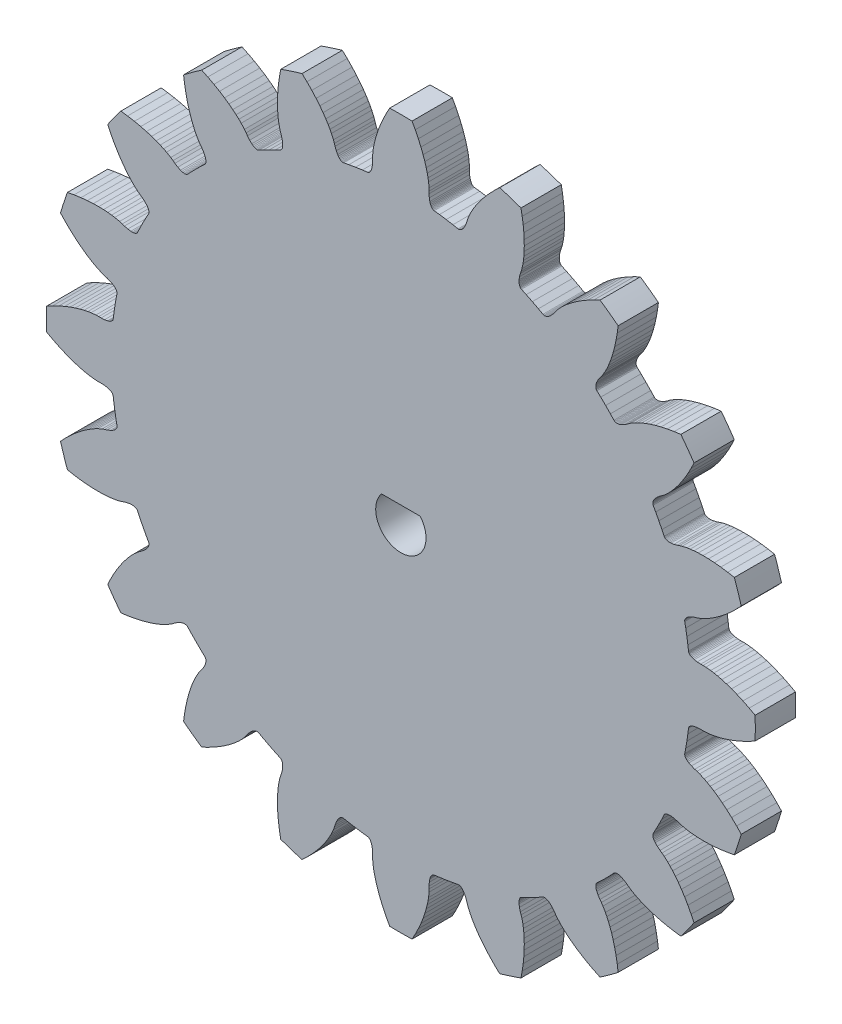
SolidWorks part; units mm, degrees
ref_plane "Front Plane" through (0, 0, 0) normal (0, 0, 1) x (1, 0, 0)
ref_plane "Top Plane" through (0, 0, 0) normal (0, 1, 0) x (1, 0, 0)
ref_plane "Right Plane" through (0, 0, 0) normal (1, 0, 0) x (0, 0, -1)
sketch "Model" plane through (0, 0, 0) normal (0, 0, 1) x (1, 0, 0)
  line L0 (41.6786, 11.6622) -> (41.0581, 11.0595)
  line L1 (41.0581, 11.0595) -> (40.4611, 10.5264)
  line L2 (40.4611, 10.5264) -> (39.8935, 10.0607)
  line L3 (39.8935, 10.0607) -> (39.3607, 9.6597)
  line L4 (39.3607, 9.6597) -> (38.8648, 9.3179)
  line L5 (38.8648, 9.3179) -> (38.4118, 9.033)
  line L6 (38.4118, 9.033) -> (38.0041, 8.7997)
  line L7 (38.0041, 8.7997) -> (37.6455, 8.6139)
  line L8 (37.6455, 8.6139) -> (37.0884, 8.3667)
  line L9 (37.0884, 8.3667) -> (36.7615, 8.2523)
  line L10 (36.7615, 8.2523) -> (36.4807, 8.1681)
  line L11 (36.4807, 8.1681) -> (36.0803, 8.0133)
  line L12 (36.0803, 8.0133) -> (35.757, 7.8422)
  line L13 (35.757, 7.8422) -> (35.6244, 7.7525)
  line L14 (35.6244, 7.7525) -> (35.5112, 7.661)
  line L15 (35.5112, 7.661) -> (35.4174, 7.5686)
  line L16 (35.4174, 7.5686) -> (35.3431, 7.476)
  line L17 (35.3431, 7.476) -> (35.2881, 7.3839)
  line L18 (35.2881, 7.3839) -> (35.2524, 7.2932)
  line L19 (35.2524, 7.2932) -> (35.236, 7.2046)
  line L20 (35.236, 7.2046) -> (35.2423, 7.0979)
  line L21 (35.2423, 7.0979) -> (35.3653, 6.4581)
  line L22 (35.3653, 6.4581) -> (35.5074, 5.6238)
  line L23 (35.5074, 5.6238) -> (35.6301, 4.7864)
  line L24 (35.6301, 4.7864) -> (35.7108, 4.1399)
  line L25 (35.7108, 4.1399) -> (35.7378, 4.0366)
  line L26 (35.7378, 4.0366) -> (35.7808, 3.9574)
  line L27 (35.7808, 3.9574) -> (35.8427, 3.8821)
  line L28 (35.8427, 3.8821) -> (35.9235, 3.8115)
  line L29 (35.9235, 3.8115) -> (36.0228, 3.7464)
  line L30 (36.0228, 3.7464) -> (36.1405, 3.6875)
  line L31 (36.1405, 3.6875) -> (36.2764, 3.6355)
  line L32 (36.2764, 3.6355) -> (36.4303, 3.5911)
  line L33 (36.4303, 3.5911) -> (36.7907, 3.5283)
  line L34 (36.7907, 3.5283) -> (37.2193, 3.5048)
  line L35 (37.2193, 3.5048) -> (37.5124, 3.5115)
  line L36 (37.5124, 3.5115) -> (37.8587, 3.5038)
  line L37 (37.8587, 3.5038) -> (38.4649, 3.4408)
  line L38 (38.4649, 3.4408) -> (38.8633, 3.3749)
  line L39 (38.8633, 3.3749) -> (39.3231, 3.279)
  line L40 (39.3231, 3.279) -> (39.842, 3.148)
  line L41 (39.842, 3.148) -> (40.4192, 2.9762)
  line L42 (40.4192, 2.9762) -> (41.0499, 2.7595)
  line L43 (41.0499, 2.7595) -> (41.7336, 2.492)
  line L44 (41.7336, 2.492) -> (42.4661, 2.1695)
  line L45 (42.4661, 2.1695) -> (43.2425, 1.788)
  line L46 (43.2425, 1.788) -> (43.978, 1.389)
  line L47 (43.978, -1.389) -> (43.2425, -1.788)
  line L48 (43.2425, -1.788) -> (42.4661, -2.1695)
  line L49 (42.4661, -2.1695) -> (41.7336, -2.492)
  line L50 (41.7336, -2.492) -> (41.0499, -2.7595)
  line L51 (41.0499, -2.7595) -> (40.4192, -2.9762)
  line L52 (40.4192, -2.9762) -> (39.842, -3.148)
  line L53 (39.842, -3.148) -> (39.3231, -3.279)
  line L54 (39.3231, -3.279) -> (38.8633, -3.3749)
  line L55 (38.8633, -3.3749) -> (38.4649, -3.4408)
  line L56 (38.4649, -3.4408) -> (37.8587, -3.5038)
  line L57 (37.8587, -3.5038) -> (37.5124, -3.5115)
  line L58 (37.5124, -3.5115) -> (37.2193, -3.5048)
  line L59 (37.2193, -3.5048) -> (36.7907, -3.5283)
  line L60 (36.7907, -3.5283) -> (36.4303, -3.5911)
  line L61 (36.4303, -3.5911) -> (36.2764, -3.6355)
  line L62 (36.2764, -3.6355) -> (36.1405, -3.6875)
  line L63 (36.1405, -3.6875) -> (36.0228, -3.7464)
  line L64 (36.0228, -3.7464) -> (35.9235, -3.8115)
  line L65 (35.9235, -3.8115) -> (35.8427, -3.8821)
  line L66 (35.8427, -3.8821) -> (35.7808, -3.9574)
  line L67 (35.7808, -3.9574) -> (35.7378, -4.0366)
  line L68 (35.7378, -4.0366) -> (35.7108, -4.1399)
  line L69 (35.7108, -4.1399) -> (35.6301, -4.7864)
  line L70 (35.6301, -4.7864) -> (35.5074, -5.6238)
  line L71 (35.5074, -5.6238) -> (35.3653, -6.4581)
  line L72 (35.3653, -6.4581) -> (35.2423, -7.0979)
  line L73 (35.2423, -7.0979) -> (35.236, -7.2046)
  line L74 (35.236, -7.2046) -> (35.2524, -7.2932)
  line L75 (35.2524, -7.2932) -> (35.2881, -7.3839)
  line L76 (35.2881, -7.3839) -> (35.3431, -7.476)
  line L77 (35.3431, -7.476) -> (35.4174, -7.5686)
  line L78 (35.4174, -7.5686) -> (35.5112, -7.661)
  line L79 (35.5112, -7.661) -> (35.6244, -7.7525)
  line L80 (35.6244, -7.7525) -> (35.757, -7.8422)
  line L81 (35.757, -7.8422) -> (36.0803, -8.0133)
  line L82 (36.0803, -8.0133) -> (36.4807, -8.1681)
  line L83 (36.4807, -8.1681) -> (36.7615, -8.2523)
  line L84 (36.7615, -8.2523) -> (37.0884, -8.3667)
  line L85 (37.0884, -8.3667) -> (37.6455, -8.6139)
  line L86 (37.6455, -8.6139) -> (38.0041, -8.7997)
  line L87 (38.0041, -8.7997) -> (38.4118, -9.033)
  line L88 (38.4118, -9.033) -> (38.8648, -9.3179)
  line L89 (38.8648, -9.3179) -> (39.3607, -9.6597)
  line L90 (39.3607, -9.6597) -> (39.8935, -10.0607)
  line L91 (39.8935, -10.0607) -> (40.4611, -10.5264)
  line L92 (40.4611, -10.5264) -> (41.0581, -11.0595)
  line L93 (41.0581, -11.0595) -> (41.6786, -11.6622)
  line L94 (41.6786, -11.6622) -> (42.2548, -12.2689)
  line L95 (41.3963, -14.911) -> (40.5736, -15.0632)
  line L96 (40.5736, -15.0632) -> (39.7173, -15.186)
  line L97 (39.7173, -15.186) -> (38.921, -15.2664)
  line L98 (38.921, -15.2664) -> (38.1881, -15.3095)
  line L99 (38.1881, -15.3095) -> (37.5212, -15.3208)
  line L100 (37.5212, -15.3208) -> (36.9192, -15.3058)
  line L101 (36.9192, -15.3058) -> (36.3852, -15.2701)
  line L102 (36.3852, -15.2701) -> (35.9183, -15.2192)
  line L103 (35.9183, -15.2192) -> (35.519, -15.1587)
  line L104 (35.519, -15.1587) -> (34.923, -15.0313)
  line L105 (34.923, -15.0313) -> (34.5913, -14.9316)
  line L106 (34.5913, -14.9316) -> (34.3146, -14.8347)
  line L107 (34.3146, -14.8347) -> (33.8997, -14.7246)
  line L108 (33.8997, -14.7246) -> (33.5375, -14.673)
  line L109 (33.5375, -14.673) -> (33.3775, -14.6676)
  line L110 (33.3775, -14.6676) -> (33.2322, -14.675)
  line L111 (33.2322, -14.675) -> (33.102, -14.6947)
  line L112 (33.102, -14.6947) -> (32.9874, -14.726)
  line L113 (32.9874, -14.726) -> (32.8888, -14.7681)
  line L114 (32.8888, -14.7681) -> (32.8066, -14.8206)
  line L115 (32.8066, -14.8206) -> (32.7413, -14.8826)
  line L116 (32.7413, -14.8826) -> (32.6837, -14.9726)
  line L117 (32.6837, -14.9726) -> (32.4071, -15.5625)
  line L118 (32.4071, -15.5625) -> (32.0317, -16.321)
  line L119 (32.0317, -16.321) -> (31.6387, -17.0705)
  line L120 (31.6387, -17.0705) -> (31.3241, -17.641)
  line L121 (31.3241, -17.641) -> (31.2851, -17.7405)
  line L122 (31.2851, -17.7405) -> (31.2733, -17.8298)
  line L123 (31.2733, -17.8298) -> (31.2792, -17.9271)
  line L124 (31.2792, -17.9271) -> (31.3031, -18.0317)
  line L125 (31.3031, -18.0317) -> (31.3451, -18.1427)
  line L126 (31.3451, -18.1427) -> (31.4057, -18.2596)
  line L127 (31.4057, -18.2596) -> (31.4851, -18.3816)
  line L128 (31.4851, -18.3816) -> (31.5835, -18.5079)
  line L129 (31.5835, -18.5079) -> (31.8382, -18.7705)
  line L130 (31.8382, -18.7705) -> (32.1711, -19.0415)
  line L131 (32.1711, -19.0415) -> (32.4121, -19.2084)
  line L132 (32.4121, -19.2084) -> (32.6878, -19.4181)
  line L133 (32.6878, -19.4181) -> (33.1412, -19.8254)
  line L134 (33.1412, -19.8254) -> (33.4248, -20.1129)
  line L135 (33.4248, -20.1129) -> (33.7404, -20.4607)
  line L136 (33.7404, -20.4607) -> (34.0832, -20.8718)
  line L137 (34.0832, -20.8718) -> (34.4492, -21.35)
  line L138 (34.4492, -21.35) -> (34.832, -21.8961)
  line L139 (34.832, -21.8961) -> (35.228, -22.5143)
  line L140 (35.228, -22.5143) -> (35.631, -23.2058)
  line L141 (35.631, -23.2058) -> (36.0349, -23.9708)
  line L142 (36.0349, -23.9708) -> (36.3954, -24.7259)
  line L143 (34.7625, -26.9734) -> (33.933, -26.8638)
  line L144 (33.933, -26.8638) -> (33.0806, -26.7161)
  line L145 (33.0806, -26.7161) -> (32.2984, -26.5465)
  line L146 (32.2984, -26.5465) -> (31.5881, -26.361)
  line L147 (31.5881, -26.361) -> (30.9504, -26.1656)
  line L148 (30.9504, -26.1656) -> (30.3825, -25.9653)
  line L149 (30.3825, -25.9653) -> (29.8857, -25.7663)
  line L150 (29.8857, -25.7663) -> (29.4573, -25.5736)
  line L151 (29.4573, -25.5736) -> (29.0963, -25.3927)
  line L152 (29.0963, -25.3927) -> (28.5688, -25.0874)
  line L153 (28.5688, -25.0874) -> (28.2841, -24.8901)
  line L154 (28.2841, -24.8901) -> (28.0509, -24.7124)
  line L155 (28.0509, -24.7124) -> (27.6904, -24.4795)
  line L156 (27.6904, -24.4795) -> (27.3619, -24.3185)
  line L157 (27.3619, -24.3185) -> (27.2114, -24.2639)
  line L158 (27.2114, -24.2639) -> (27.0708, -24.2261)
  line L159 (27.0708, -24.2261) -> (26.941, -24.2046)
  line L160 (26.941, -24.2046) -> (26.8223, -24.1989)
  line L161 (26.8223, -24.1989) -> (26.7155, -24.2085)
  line L162 (26.7155, -24.2085) -> (26.6212, -24.233)
  line L163 (26.6212, -24.233) -> (26.5398, -24.2718)
  line L164 (26.5398, -24.2718) -> (26.4573, -24.3396)
  line L165 (26.4573, -24.3396) -> (26.0119, -24.8151)
  line L166 (26.0119, -24.8151) -> (25.4205, -25.4205)
  line L167 (25.4205, -25.4205) -> (24.8151, -26.0119)
  line L168 (24.8151, -26.0119) -> (24.3396, -26.4573)
  line L169 (24.3396, -26.4573) -> (24.2718, -26.5398)
  line L170 (24.2718, -26.5398) -> (24.233, -26.6212)
  line L171 (24.233, -26.6212) -> (24.2085, -26.7155)
  line L172 (24.2085, -26.7155) -> (24.1989, -26.8223)
  line L173 (24.1989, -26.8223) -> (24.2046, -26.941)
  line L174 (24.2046, -26.941) -> (24.2261, -27.0708)
  line L175 (24.2261, -27.0708) -> (24.2639, -27.2114)
  line L176 (24.2639, -27.2114) -> (24.3185, -27.3619)
  line L177 (24.3185, -27.3619) -> (24.4795, -27.6904)
  line L178 (24.4795, -27.6904) -> (24.7124, -28.0509)
  line L179 (24.7124, -28.0509) -> (24.8901, -28.2841)
  line L180 (24.8901, -28.2841) -> (25.0874, -28.5688)
  line L181 (25.0874, -28.5688) -> (25.3927, -29.0963)
  line L182 (25.3927, -29.0963) -> (25.5736, -29.4573)
  line L183 (25.5736, -29.4573) -> (25.7663, -29.8857)
  line L184 (25.7663, -29.8857) -> (25.9653, -30.3825)
  line L185 (25.9653, -30.3825) -> (26.1656, -30.9504)
  line L186 (26.1656, -30.9504) -> (26.361, -31.5881)
  line L187 (26.361, -31.5881) -> (26.5465, -32.2984)
  line L188 (26.5465, -32.2984) -> (26.7161, -33.0806)
  line L189 (26.7161, -33.0806) -> (26.8638, -33.933)
  line L190 (26.8638, -33.933) -> (26.9734, -34.7625)
  line L191 (24.7259, -36.3954) -> (23.9708, -36.0349)
  line L192 (23.9708, -36.0349) -> (23.2058, -35.631)
  line L193 (23.2058, -35.631) -> (22.5143, -35.228)
  line L194 (22.5143, -35.228) -> (21.8961, -34.832)
  line L195 (21.8961, -34.832) -> (21.35, -34.4492)
  line L196 (21.35, -34.4492) -> (20.8718, -34.0832)
  line L197 (20.8718, -34.0832) -> (20.4607, -33.7404)
  line L198 (20.4607, -33.7404) -> (20.1129, -33.4248)
  line L199 (20.1129, -33.4248) -> (19.8254, -33.1412)
  line L200 (19.8254, -33.1412) -> (19.4181, -32.6878)
  line L201 (19.4181, -32.6878) -> (19.2084, -32.4121)
  line L202 (19.2084, -32.4121) -> (19.0415, -32.1711)
  line L203 (19.0415, -32.1711) -> (18.7705, -31.8382)
  line L204 (18.7705, -31.8382) -> (18.5079, -31.5835)
  line L205 (18.5079, -31.5835) -> (18.3816, -31.4851)
  line L206 (18.3816, -31.4851) -> (18.2596, -31.4057)
  line L207 (18.2596, -31.4057) -> (18.1427, -31.3451)
  line L208 (18.1427, -31.3451) -> (18.0317, -31.3031)
  line L209 (18.0317, -31.3031) -> (17.9271, -31.2792)
  line L210 (17.9271, -31.2792) -> (17.8298, -31.2733)
  line L211 (17.8298, -31.2733) -> (17.7405, -31.2851)
  line L212 (17.7405, -31.2851) -> (17.641, -31.3241)
  line L213 (17.641, -31.3241) -> (17.0705, -31.6387)
  line L214 (17.0705, -31.6387) -> (16.321, -32.0317)
  line L215 (16.321, -32.0317) -> (15.5625, -32.4071)
  line L216 (15.5625, -32.4071) -> (14.9726, -32.6837)
  line L217 (14.9726, -32.6837) -> (14.8826, -32.7413)
  line L218 (14.8826, -32.7413) -> (14.8206, -32.8066)
  line L219 (14.8206, -32.8066) -> (14.7681, -32.8888)
  line L220 (14.7681, -32.8888) -> (14.726, -32.9874)
  line L221 (14.726, -32.9874) -> (14.6947, -33.102)
  line L222 (14.6947, -33.102) -> (14.675, -33.2322)
  line L223 (14.675, -33.2322) -> (14.6676, -33.3775)
  line L224 (14.6676, -33.3775) -> (14.673, -33.5375)
  line L225 (14.673, -33.5375) -> (14.7246, -33.8997)
  line L226 (14.7246, -33.8997) -> (14.8347, -34.3146)
  line L227 (14.8347, -34.3146) -> (14.9316, -34.5913)
  line L228 (14.9316, -34.5913) -> (15.0313, -34.923)
  line L229 (15.0313, -34.923) -> (15.1587, -35.519)
  line L230 (15.1587, -35.519) -> (15.2192, -35.9183)
  line L231 (15.2192, -35.9183) -> (15.2701, -36.3852)
  line L232 (15.2701, -36.3852) -> (15.3058, -36.9192)
  line L233 (15.3058, -36.9192) -> (15.3208, -37.5212)
  line L234 (15.3208, -37.5212) -> (15.3095, -38.1881)
  line L235 (15.3095, -38.1881) -> (15.2664, -38.921)
  line L236 (15.2664, -38.921) -> (15.186, -39.7173)
  line L237 (15.186, -39.7173) -> (15.0632, -40.5736)
  line L238 (15.0632, -40.5736) -> (14.911, -41.3963)
  line L239 (12.2689, -42.2548) -> (11.6622, -41.6786)
  line L240 (11.6622, -41.6786) -> (11.0595, -41.0581)
  line L241 (11.0595, -41.0581) -> (10.5264, -40.4611)
  line L242 (10.5264, -40.4611) -> (10.0607, -39.8935)
  line L243 (10.0607, -39.8935) -> (9.6597, -39.3607)
  line L244 (9.6597, -39.3607) -> (9.3179, -38.8648)
  line L245 (9.3179, -38.8648) -> (9.033, -38.4118)
  line L246 (9.033, -38.4118) -> (8.7997, -38.0041)
  line L247 (8.7997, -38.0041) -> (8.6139, -37.6455)
  line L248 (8.6139, -37.6455) -> (8.3667, -37.0884)
  line L249 (8.3667, -37.0884) -> (8.2523, -36.7615)
  line L250 (8.2523, -36.7615) -> (8.1681, -36.4807)
  line L251 (8.1681, -36.4807) -> (8.0133, -36.0803)
  line L252 (8.0133, -36.0803) -> (7.8422, -35.757)
  line L253 (7.8422, -35.757) -> (7.7525, -35.6244)
  line L254 (7.7525, -35.6244) -> (7.661, -35.5112)
  line L255 (7.661, -35.5112) -> (7.5686, -35.4174)
  line L256 (7.5686, -35.4174) -> (7.476, -35.3431)
  line L257 (7.476, -35.3431) -> (7.3839, -35.2881)
  line L258 (7.3839, -35.2881) -> (7.2932, -35.2524)
  line L259 (7.2932, -35.2524) -> (7.2046, -35.236)
  line L260 (7.2046, -35.236) -> (7.0979, -35.2423)
  line L261 (7.0979, -35.2423) -> (6.4581, -35.3653)
  line L262 (6.4581, -35.3653) -> (5.6238, -35.5074)
  line L263 (5.6238, -35.5074) -> (4.7864, -35.6301)
  line L264 (4.7864, -35.6301) -> (4.1399, -35.7108)
  line L265 (4.1399, -35.7108) -> (4.0366, -35.7378)
  line L266 (4.0366, -35.7378) -> (3.9574, -35.7808)
  line L267 (3.9574, -35.7808) -> (3.8821, -35.8427)
  line L268 (3.8821, -35.8427) -> (3.8115, -35.9235)
  line L269 (3.8115, -35.9235) -> (3.7464, -36.0228)
  line L270 (3.7464, -36.0228) -> (3.6875, -36.1405)
  line L271 (3.6875, -36.1405) -> (3.6355, -36.2764)
  line L272 (3.6355, -36.2764) -> (3.5911, -36.4303)
  line L273 (3.5911, -36.4303) -> (3.5283, -36.7907)
  line L274 (3.5283, -36.7907) -> (3.5048, -37.2193)
  line L275 (3.5048, -37.2193) -> (3.5115, -37.5124)
  line L276 (3.5115, -37.5124) -> (3.5038, -37.8587)
  line L277 (3.5038, -37.8587) -> (3.4408, -38.4649)
  line L278 (3.4408, -38.4649) -> (3.3749, -38.8633)
  line L279 (3.3749, -38.8633) -> (3.279, -39.3231)
  line L280 (3.279, -39.3231) -> (3.148, -39.842)
  line L281 (3.148, -39.842) -> (2.9762, -40.4192)
  line L282 (2.9762, -40.4192) -> (2.7595, -41.0499)
  line L283 (2.7595, -41.0499) -> (2.492, -41.7336)
  line L284 (2.492, -41.7336) -> (2.1695, -42.4661)
  line L285 (2.1695, -42.4661) -> (1.788, -43.2425)
  line L286 (1.788, -43.2425) -> (1.389, -43.978)
  line L287 (-1.389, -43.978) -> (-1.788, -43.2425)
  line L288 (-1.788, -43.2425) -> (-2.1695, -42.4661)
  line L289 (-2.1695, -42.4661) -> (-2.492, -41.7336)
  line L290 (-2.492, -41.7336) -> (-2.7595, -41.0499)
  line L291 (-2.7595, -41.0499) -> (-2.9762, -40.4192)
  line L292 (-2.9762, -40.4192) -> (-3.148, -39.842)
  line L293 (-3.148, -39.842) -> (-3.279, -39.3231)
  line L294 (-3.279, -39.3231) -> (-3.3749, -38.8633)
  line L295 (-3.3749, -38.8633) -> (-3.4408, -38.4649)
  line L296 (-3.4408, -38.4649) -> (-3.5038, -37.8587)
  line L297 (-3.5038, -37.8587) -> (-3.5115, -37.5124)
  line L298 (-3.5115, -37.5124) -> (-3.5048, -37.2193)
  line L299 (-3.5048, -37.2193) -> (-3.5283, -36.7907)
  line L300 (-3.5283, -36.7907) -> (-3.5911, -36.4303)
  line L301 (-3.5911, -36.4303) -> (-3.6355, -36.2764)
  line L302 (-3.6355, -36.2764) -> (-3.6875, -36.1405)
  line L303 (-3.6875, -36.1405) -> (-3.7464, -36.0228)
  line L304 (-3.7464, -36.0228) -> (-3.8115, -35.9235)
  line L305 (-3.8115, -35.9235) -> (-3.8821, -35.8427)
  line L306 (-3.8821, -35.8427) -> (-3.9574, -35.7808)
  line L307 (-3.9574, -35.7808) -> (-4.0366, -35.7378)
  line L308 (-4.0366, -35.7378) -> (-4.1399, -35.7108)
  line L309 (-4.1399, -35.7108) -> (-4.7864, -35.6301)
  line L310 (-4.7864, -35.6301) -> (-5.6238, -35.5074)
  line L311 (-5.6238, -35.5074) -> (-6.4581, -35.3653)
  line L312 (-6.4581, -35.3653) -> (-7.0979, -35.2423)
  line L313 (-7.0979, -35.2423) -> (-7.2046, -35.236)
  line L314 (-7.2046, -35.236) -> (-7.2932, -35.2524)
  line L315 (-7.2932, -35.2524) -> (-7.3839, -35.2881)
  line L316 (-7.3839, -35.2881) -> (-7.476, -35.3431)
  line L317 (-7.476, -35.3431) -> (-7.5686, -35.4174)
  line L318 (-7.5686, -35.4174) -> (-7.661, -35.5112)
  line L319 (-7.661, -35.5112) -> (-7.7525, -35.6244)
  line L320 (-7.7525, -35.6244) -> (-7.8422, -35.757)
  line L321 (-7.8422, -35.757) -> (-8.0133, -36.0803)
  line L322 (-8.0133, -36.0803) -> (-8.1681, -36.4807)
  line L323 (-8.1681, -36.4807) -> (-8.2523, -36.7615)
  line L324 (-8.2523, -36.7615) -> (-8.3667, -37.0884)
  line L325 (-8.3667, -37.0884) -> (-8.6139, -37.6455)
  line L326 (-8.6139, -37.6455) -> (-8.7997, -38.0041)
  line L327 (-8.7997, -38.0041) -> (-9.033, -38.4118)
  line L328 (-9.033, -38.4118) -> (-9.3179, -38.8648)
  line L329 (-9.3179, -38.8648) -> (-9.6597, -39.3607)
  line L330 (-9.6597, -39.3607) -> (-10.0607, -39.8935)
  line L331 (-10.0607, -39.8935) -> (-10.5264, -40.4611)
  line L332 (-10.5264, -40.4611) -> (-11.0595, -41.0581)
  line L333 (-11.0595, -41.0581) -> (-11.6622, -41.6786)
  line L334 (-11.6622, -41.6786) -> (-12.2689, -42.2548)
  line L335 (-14.911, -41.3963) -> (-15.0632, -40.5736)
  line L336 (-15.0632, -40.5736) -> (-15.186, -39.7173)
  line L337 (-15.186, -39.7173) -> (-15.2664, -38.921)
  line L338 (-15.2664, -38.921) -> (-15.3095, -38.1881)
  line L339 (-15.3095, -38.1881) -> (-15.3208, -37.5212)
  line L340 (-15.3208, -37.5212) -> (-15.3058, -36.9192)
  line L341 (-15.3058, -36.9192) -> (-15.2701, -36.3852)
  line L342 (-15.2701, -36.3852) -> (-15.2192, -35.9183)
  line L343 (-15.2192, -35.9183) -> (-15.1587, -35.519)
  line L344 (-15.1587, -35.519) -> (-15.0313, -34.923)
  line L345 (-15.0313, -34.923) -> (-14.9316, -34.5913)
  line L346 (-14.9316, -34.5913) -> (-14.8347, -34.3146)
  line L347 (-14.8347, -34.3146) -> (-14.7246, -33.8997)
  line L348 (-14.7246, -33.8997) -> (-14.673, -33.5375)
  line L349 (-14.673, -33.5375) -> (-14.6676, -33.3775)
  line L350 (-14.6676, -33.3775) -> (-14.675, -33.2322)
  line L351 (-14.675, -33.2322) -> (-14.6947, -33.102)
  line L352 (-14.6947, -33.102) -> (-14.726, -32.9874)
  line L353 (-14.726, -32.9874) -> (-14.7681, -32.8888)
  line L354 (-14.7681, -32.8888) -> (-14.8206, -32.8066)
  line L355 (-14.8206, -32.8066) -> (-14.8826, -32.7413)
  line L356 (-14.8826, -32.7413) -> (-14.9726, -32.6837)
  line L357 (-14.9726, -32.6837) -> (-15.5625, -32.4071)
  line L358 (-15.5625, -32.4071) -> (-16.321, -32.0317)
  line L359 (-16.321, -32.0317) -> (-17.0705, -31.6387)
  line L360 (-17.0705, -31.6387) -> (-17.641, -31.3241)
  line L361 (-17.641, -31.3241) -> (-17.7405, -31.2851)
  line L362 (-17.7405, -31.2851) -> (-17.8298, -31.2733)
  line L363 (-17.8298, -31.2733) -> (-17.9271, -31.2792)
  line L364 (-17.9271, -31.2792) -> (-18.0317, -31.3031)
  line L365 (-18.0317, -31.3031) -> (-18.1427, -31.3451)
  line L366 (-18.1427, -31.3451) -> (-18.2596, -31.4057)
  line L367 (-18.2596, -31.4057) -> (-18.3816, -31.4851)
  line L368 (-18.3816, -31.4851) -> (-18.5079, -31.5835)
  line L369 (-18.5079, -31.5835) -> (-18.7705, -31.8382)
  line L370 (-18.7705, -31.8382) -> (-19.0415, -32.1711)
  line L371 (-19.0415, -32.1711) -> (-19.2084, -32.4121)
  line L372 (-19.2084, -32.4121) -> (-19.4181, -32.6878)
  line L373 (-19.4181, -32.6878) -> (-19.8254, -33.1412)
  line L374 (-19.8254, -33.1412) -> (-20.1129, -33.4248)
  line L375 (-20.1129, -33.4248) -> (-20.4607, -33.7404)
  line L376 (-20.4607, -33.7404) -> (-20.8718, -34.0832)
  line L377 (-20.8718, -34.0832) -> (-21.35, -34.4492)
  line L378 (-21.35, -34.4492) -> (-21.8961, -34.832)
  line L379 (-21.8961, -34.832) -> (-22.5143, -35.228)
  line L380 (-22.5143, -35.228) -> (-23.2058, -35.631)
  line L381 (-23.2058, -35.631) -> (-23.9708, -36.0349)
  line L382 (-23.9708, -36.0349) -> (-24.7259, -36.3954)
  line L383 (-26.9734, -34.7625) -> (-26.8638, -33.933)
  line L384 (-26.8638, -33.933) -> (-26.7161, -33.0806)
  line L385 (-26.7161, -33.0806) -> (-26.5465, -32.2984)
  line L386 (-26.5465, -32.2984) -> (-26.361, -31.5881)
  line L387 (-26.361, -31.5881) -> (-26.1656, -30.9504)
  line L388 (-26.1656, -30.9504) -> (-25.9653, -30.3825)
  line L389 (-25.9653, -30.3825) -> (-25.7663, -29.8857)
  line L390 (-25.7663, -29.8857) -> (-25.5736, -29.4573)
  line L391 (-25.5736, -29.4573) -> (-25.3927, -29.0963)
  line L392 (-25.3927, -29.0963) -> (-25.0874, -28.5688)
  line L393 (-25.0874, -28.5688) -> (-24.8901, -28.2841)
  line L394 (-24.8901, -28.2841) -> (-24.7124, -28.0509)
  line L395 (-24.7124, -28.0509) -> (-24.4795, -27.6904)
  line L396 (-24.4795, -27.6904) -> (-24.3185, -27.3619)
  line L397 (-24.3185, -27.3619) -> (-24.2639, -27.2114)
  line L398 (-24.2639, -27.2114) -> (-24.2261, -27.0708)
  line L399 (-24.2261, -27.0708) -> (-24.2046, -26.941)
  line L400 (-24.2046, -26.941) -> (-24.1989, -26.8223)
  line L401 (-24.1989, -26.8223) -> (-24.2085, -26.7155)
  line L402 (-24.2085, -26.7155) -> (-24.233, -26.6212)
  line L403 (-24.233, -26.6212) -> (-24.2718, -26.5398)
  line L404 (-24.2718, -26.5398) -> (-24.3396, -26.4573)
  line L405 (-24.3396, -26.4573) -> (-24.8151, -26.0119)
  line L406 (-24.8151, -26.0119) -> (-25.4205, -25.4205)
  line L407 (-25.4205, -25.4205) -> (-26.0119, -24.8151)
  line L408 (-26.0119, -24.8151) -> (-26.4573, -24.3396)
  line L409 (-26.4573, -24.3396) -> (-26.5398, -24.2718)
  line L410 (-26.5398, -24.2718) -> (-26.6212, -24.233)
  line L411 (-26.6212, -24.233) -> (-26.7155, -24.2085)
  line L412 (-26.7155, -24.2085) -> (-26.8223, -24.1989)
  line L413 (-26.8223, -24.1989) -> (-26.941, -24.2046)
  line L414 (-26.941, -24.2046) -> (-27.0708, -24.2261)
  line L415 (-27.0708, -24.2261) -> (-27.2114, -24.2639)
  line L416 (-27.2114, -24.2639) -> (-27.3619, -24.3185)
  line L417 (-27.3619, -24.3185) -> (-27.6904, -24.4795)
  line L418 (-27.6904, -24.4795) -> (-28.0509, -24.7124)
  line L419 (-28.0509, -24.7124) -> (-28.2841, -24.8901)
  line L420 (-28.2841, -24.8901) -> (-28.5688, -25.0874)
  line L421 (-28.5688, -25.0874) -> (-29.0963, -25.3927)
  line L422 (-29.0963, -25.3927) -> (-29.4573, -25.5736)
  line L423 (-29.4573, -25.5736) -> (-29.8857, -25.7663)
  line L424 (-29.8857, -25.7663) -> (-30.3825, -25.9653)
  line L425 (-30.3825, -25.9653) -> (-30.9504, -26.1656)
  line L426 (-30.9504, -26.1656) -> (-31.5881, -26.361)
  line L427 (-31.5881, -26.361) -> (-32.2984, -26.5465)
  line L428 (-32.2984, -26.5465) -> (-33.0806, -26.7161)
  line L429 (-33.0806, -26.7161) -> (-33.933, -26.8638)
  line L430 (-33.933, -26.8638) -> (-34.7625, -26.9734)
  line L431 (-36.3954, -24.7259) -> (-36.0349, -23.9708)
  line L432 (-36.0349, -23.9708) -> (-35.631, -23.2058)
  line L433 (-35.631, -23.2058) -> (-35.228, -22.5143)
  line L434 (-35.228, -22.5143) -> (-34.832, -21.8961)
  line L435 (-34.832, -21.8961) -> (-34.4492, -21.35)
  line L436 (-34.4492, -21.35) -> (-34.0832, -20.8718)
  line L437 (-34.0832, -20.8718) -> (-33.7404, -20.4607)
  line L438 (-33.7404, -20.4607) -> (-33.4248, -20.1129)
  line L439 (-33.4248, -20.1129) -> (-33.1412, -19.8254)
  line L440 (-33.1412, -19.8254) -> (-32.6878, -19.4181)
  line L441 (-32.6878, -19.4181) -> (-32.4121, -19.2084)
  line L442 (-32.4121, -19.2084) -> (-32.1711, -19.0415)
  line L443 (-32.1711, -19.0415) -> (-31.8382, -18.7705)
  line L444 (-31.8382, -18.7705) -> (-31.5835, -18.5079)
  line L445 (-31.5835, -18.5079) -> (-31.4851, -18.3816)
  line L446 (-31.4851, -18.3816) -> (-31.4057, -18.2596)
  line L447 (-31.4057, -18.2596) -> (-31.3451, -18.1427)
  line L448 (-31.3451, -18.1427) -> (-31.3031, -18.0317)
  line L449 (-31.3031, -18.0317) -> (-31.2792, -17.9271)
  line L450 (-31.2792, -17.9271) -> (-31.2733, -17.8298)
  line L451 (-31.2733, -17.8298) -> (-31.2851, -17.7405)
  line L452 (-31.2851, -17.7405) -> (-31.3241, -17.641)
  line L453 (-31.3241, -17.641) -> (-31.6387, -17.0705)
  line L454 (-31.6387, -17.0705) -> (-32.0317, -16.321)
  line L455 (-32.0317, -16.321) -> (-32.4071, -15.5625)
  line L456 (-32.4071, -15.5625) -> (-32.6837, -14.9726)
  line L457 (-32.6837, -14.9726) -> (-32.7413, -14.8826)
  line L458 (-32.7413, -14.8826) -> (-32.8066, -14.8206)
  line L459 (-32.8066, -14.8206) -> (-32.8888, -14.7681)
  line L460 (-32.8888, -14.7681) -> (-32.9874, -14.726)
  line L461 (-32.9874, -14.726) -> (-33.102, -14.6947)
  line L462 (-33.102, -14.6947) -> (-33.2322, -14.675)
  line L463 (-33.2322, -14.675) -> (-33.3775, -14.6676)
  line L464 (-33.3775, -14.6676) -> (-33.5375, -14.673)
  line L465 (-33.5375, -14.673) -> (-33.8997, -14.7246)
  line L466 (-33.8997, -14.7246) -> (-34.3146, -14.8347)
  line L467 (-34.3146, -14.8347) -> (-34.5913, -14.9316)
  line L468 (-34.5913, -14.9316) -> (-34.923, -15.0313)
  line L469 (-34.923, -15.0313) -> (-35.519, -15.1587)
  line L470 (-35.519, -15.1587) -> (-35.9183, -15.2192)
  line L471 (-35.9183, -15.2192) -> (-36.3852, -15.2701)
  line L472 (-36.3852, -15.2701) -> (-36.9192, -15.3058)
  line L473 (-36.9192, -15.3058) -> (-37.5212, -15.3208)
  line L474 (-37.5212, -15.3208) -> (-38.1881, -15.3095)
  line L475 (-38.1881, -15.3095) -> (-38.921, -15.2664)
  line L476 (-38.921, -15.2664) -> (-39.7173, -15.186)
  line L477 (-39.7173, -15.186) -> (-40.5736, -15.0632)
  line L478 (-40.5736, -15.0632) -> (-41.3963, -14.911)
  line L479 (-42.2548, -12.2689) -> (-41.6786, -11.6622)
  line L480 (-41.6786, -11.6622) -> (-41.0581, -11.0595)
  line L481 (-41.0581, -11.0595) -> (-40.4611, -10.5264)
  line L482 (-40.4611, -10.5264) -> (-39.8935, -10.0607)
  line L483 (-39.8935, -10.0607) -> (-39.3607, -9.6597)
  line L484 (-39.3607, -9.6597) -> (-38.8648, -9.3179)
  line L485 (-38.8648, -9.3179) -> (-38.4118, -9.033)
  line L486 (-38.4118, -9.033) -> (-38.0041, -8.7997)
  line L487 (-38.0041, -8.7997) -> (-37.6455, -8.6139)
  line L488 (-37.6455, -8.6139) -> (-37.0884, -8.3667)
  line L489 (-37.0884, -8.3667) -> (-36.7615, -8.2523)
  line L490 (-36.7615, -8.2523) -> (-36.4807, -8.1681)
  line L491 (-36.4807, -8.1681) -> (-36.0803, -8.0133)
  line L492 (-36.0803, -8.0133) -> (-35.757, -7.8422)
  line L493 (-35.757, -7.8422) -> (-35.6244, -7.7525)
  line L494 (-35.6244, -7.7525) -> (-35.5112, -7.661)
  line L495 (-35.5112, -7.661) -> (-35.4174, -7.5686)
  line L496 (-35.4174, -7.5686) -> (-35.3431, -7.476)
  line L497 (-35.3431, -7.476) -> (-35.2881, -7.3839)
  line L498 (-35.2881, -7.3839) -> (-35.2524, -7.2932)
  line L499 (-35.2524, -7.2932) -> (-35.236, -7.2046)
  line L500 (-35.236, -7.2046) -> (-35.2423, -7.0979)
  line L501 (-35.2423, -7.0979) -> (-35.3653, -6.4581)
  line L502 (-35.3653, -6.4581) -> (-35.5074, -5.6238)
  line L503 (-35.5074, -5.6238) -> (-35.6301, -4.7864)
  line L504 (-35.6301, -4.7864) -> (-35.7108, -4.1399)
  line L505 (-35.7108, -4.1399) -> (-35.7378, -4.0366)
  line L506 (-35.7378, -4.0366) -> (-35.7808, -3.9574)
  line L507 (-35.7808, -3.9574) -> (-35.8427, -3.8821)
  line L508 (-35.8427, -3.8821) -> (-35.9235, -3.8115)
  line L509 (-35.9235, -3.8115) -> (-36.0228, -3.7464)
  line L510 (-36.0228, -3.7464) -> (-36.1405, -3.6875)
  line L511 (-36.1405, -3.6875) -> (-36.2764, -3.6355)
  line L512 (-36.2764, -3.6355) -> (-36.4303, -3.5911)
  line L513 (-36.4303, -3.5911) -> (-36.7907, -3.5283)
  line L514 (-36.7907, -3.5283) -> (-37.2193, -3.5048)
  line L515 (-37.2193, -3.5048) -> (-37.5124, -3.5115)
  line L516 (-37.5124, -3.5115) -> (-37.8587, -3.5038)
  line L517 (-37.8587, -3.5038) -> (-38.4649, -3.4408)
  line L518 (-38.4649, -3.4408) -> (-38.8633, -3.3749)
  line L519 (-38.8633, -3.3749) -> (-39.3231, -3.279)
  line L520 (-39.3231, -3.279) -> (-39.842, -3.148)
  line L521 (-39.842, -3.148) -> (-40.4192, -2.9762)
  line L522 (-40.4192, -2.9762) -> (-41.0499, -2.7595)
  line L523 (-41.0499, -2.7595) -> (-41.7336, -2.492)
  line L524 (-41.7336, -2.492) -> (-42.4661, -2.1695)
  line L525 (-42.4661, -2.1695) -> (-43.2425, -1.788)
  line L526 (-43.2425, -1.788) -> (-43.978, -1.389)
  line L527 (-43.978, 1.389) -> (-43.2425, 1.788)
  line L528 (-43.2425, 1.788) -> (-42.4661, 2.1695)
  line L529 (-42.4661, 2.1695) -> (-41.7336, 2.492)
  line L530 (-41.7336, 2.492) -> (-41.0499, 2.7595)
  line L531 (-41.0499, 2.7595) -> (-40.4192, 2.9762)
  line L532 (-40.4192, 2.9762) -> (-39.842, 3.148)
  line L533 (-39.842, 3.148) -> (-39.3231, 3.279)
  line L534 (-39.3231, 3.279) -> (-38.8633, 3.3749)
  line L535 (-38.8633, 3.3749) -> (-38.4649, 3.4408)
  line L536 (-38.4649, 3.4408) -> (-37.8587, 3.5038)
  line L537 (-37.8587, 3.5038) -> (-37.5124, 3.5115)
  line L538 (-37.5124, 3.5115) -> (-37.2193, 3.5048)
  line L539 (-37.2193, 3.5048) -> (-36.7907, 3.5283)
  line L540 (-36.7907, 3.5283) -> (-36.4303, 3.5911)
  line L541 (-36.4303, 3.5911) -> (-36.2764, 3.6355)
  line L542 (-36.2764, 3.6355) -> (-36.1405, 3.6875)
  line L543 (-36.1405, 3.6875) -> (-36.0228, 3.7464)
  line L544 (-36.0228, 3.7464) -> (-35.9235, 3.8115)
  line L545 (-35.9235, 3.8115) -> (-35.8427, 3.8821)
  line L546 (-35.8427, 3.8821) -> (-35.7808, 3.9574)
  line L547 (-35.7808, 3.9574) -> (-35.7378, 4.0366)
  line L548 (-35.7378, 4.0366) -> (-35.7108, 4.1399)
  line L549 (-35.7108, 4.1399) -> (-35.6301, 4.7864)
  line L550 (-35.6301, 4.7864) -> (-35.5074, 5.6238)
  line L551 (-35.5074, 5.6238) -> (-35.3653, 6.4581)
  line L552 (-35.3653, 6.4581) -> (-35.2423, 7.0979)
  line L553 (-35.2423, 7.0979) -> (-35.236, 7.2046)
  line L554 (-35.236, 7.2046) -> (-35.2524, 7.2932)
  line L555 (-35.2524, 7.2932) -> (-35.2881, 7.3839)
  line L556 (-35.2881, 7.3839) -> (-35.3431, 7.476)
  line L557 (-35.3431, 7.476) -> (-35.4174, 7.5686)
  line L558 (-35.4174, 7.5686) -> (-35.5112, 7.661)
  line L559 (-35.5112, 7.661) -> (-35.6244, 7.7525)
  line L560 (-35.6244, 7.7525) -> (-35.757, 7.8422)
  line L561 (-35.757, 7.8422) -> (-36.0803, 8.0133)
  line L562 (-36.0803, 8.0133) -> (-36.4807, 8.1681)
  line L563 (-36.4807, 8.1681) -> (-36.7615, 8.2523)
  line L564 (-36.7615, 8.2523) -> (-37.0884, 8.3667)
  line L565 (-37.0884, 8.3667) -> (-37.6455, 8.6139)
  line L566 (-37.6455, 8.6139) -> (-38.0041, 8.7997)
  line L567 (-38.0041, 8.7997) -> (-38.4118, 9.033)
  line L568 (-38.4118, 9.033) -> (-38.8648, 9.3179)
  line L569 (-38.8648, 9.3179) -> (-39.3607, 9.6597)
  line L570 (-39.3607, 9.6597) -> (-39.8935, 10.0607)
  line L571 (-39.8935, 10.0607) -> (-40.4611, 10.5264)
  line L572 (-40.4611, 10.5264) -> (-41.0581, 11.0595)
  line L573 (-41.0581, 11.0595) -> (-41.6786, 11.6622)
  line L574 (-41.6786, 11.6622) -> (-42.2548, 12.2689)
  line L575 (-41.3963, 14.911) -> (-40.5736, 15.0632)
  line L576 (-40.5736, 15.0632) -> (-39.7173, 15.186)
  line L577 (-39.7173, 15.186) -> (-38.921, 15.2664)
  line L578 (-38.921, 15.2664) -> (-38.1881, 15.3095)
  line L579 (-38.1881, 15.3095) -> (-37.5212, 15.3208)
  line L580 (-37.5212, 15.3208) -> (-36.9192, 15.3058)
  line L581 (-36.9192, 15.3058) -> (-36.3852, 15.2701)
  line L582 (-36.3852, 15.2701) -> (-35.9183, 15.2192)
  line L583 (-35.9183, 15.2192) -> (-35.519, 15.1587)
  line L584 (-35.519, 15.1587) -> (-34.923, 15.0313)
  line L585 (-34.923, 15.0313) -> (-34.5913, 14.9316)
  line L586 (-34.5913, 14.9316) -> (-34.3146, 14.8347)
  line L587 (-34.3146, 14.8347) -> (-33.8997, 14.7246)
  line L588 (-33.8997, 14.7246) -> (-33.5375, 14.673)
  line L589 (-33.5375, 14.673) -> (-33.3775, 14.6676)
  line L590 (-33.3775, 14.6676) -> (-33.2322, 14.675)
  line L591 (-33.2322, 14.675) -> (-33.102, 14.6947)
  line L592 (-33.102, 14.6947) -> (-32.9874, 14.726)
  line L593 (-32.9874, 14.726) -> (-32.8888, 14.7681)
  line L594 (-32.8888, 14.7681) -> (-32.8066, 14.8206)
  line L595 (-32.8066, 14.8206) -> (-32.7413, 14.8826)
  line L596 (-32.7413, 14.8826) -> (-32.6837, 14.9726)
  line L597 (-32.6837, 14.9726) -> (-32.4071, 15.5625)
  line L598 (-32.4071, 15.5625) -> (-32.0317, 16.321)
  line L599 (-32.0317, 16.321) -> (-31.6387, 17.0705)
  line L600 (-31.6387, 17.0705) -> (-31.3241, 17.641)
  line L601 (-31.3241, 17.641) -> (-31.2851, 17.7405)
  line L602 (-31.2851, 17.7405) -> (-31.2733, 17.8298)
  line L603 (-31.2733, 17.8298) -> (-31.2792, 17.9271)
  line L604 (-31.2792, 17.9271) -> (-31.3031, 18.0317)
  line L605 (-31.3031, 18.0317) -> (-31.3451, 18.1427)
  line L606 (-31.3451, 18.1427) -> (-31.4057, 18.2596)
  line L607 (-31.4057, 18.2596) -> (-31.4851, 18.3816)
  line L608 (-31.4851, 18.3816) -> (-31.5835, 18.5079)
  line L609 (-31.5835, 18.5079) -> (-31.8382, 18.7705)
  line L610 (-31.8382, 18.7705) -> (-32.1711, 19.0415)
  line L611 (-32.1711, 19.0415) -> (-32.4121, 19.2084)
  line L612 (-32.4121, 19.2084) -> (-32.6878, 19.4181)
  line L613 (-32.6878, 19.4181) -> (-33.1412, 19.8254)
  line L614 (-33.1412, 19.8254) -> (-33.4248, 20.1129)
  line L615 (-33.4248, 20.1129) -> (-33.7404, 20.4607)
  line L616 (-33.7404, 20.4607) -> (-34.0832, 20.8718)
  line L617 (-34.0832, 20.8718) -> (-34.4492, 21.35)
  line L618 (-34.4492, 21.35) -> (-34.832, 21.8961)
  line L619 (-34.832, 21.8961) -> (-35.228, 22.5143)
  line L620 (-35.228, 22.5143) -> (-35.631, 23.2058)
  line L621 (-35.631, 23.2058) -> (-36.0349, 23.9708)
  line L622 (-36.0349, 23.9708) -> (-36.3954, 24.7259)
  line L623 (-34.7625, 26.9734) -> (-33.933, 26.8638)
  line L624 (-33.933, 26.8638) -> (-33.0806, 26.7161)
  line L625 (-33.0806, 26.7161) -> (-32.2984, 26.5465)
  line L626 (-32.2984, 26.5465) -> (-31.5881, 26.361)
  line L627 (-31.5881, 26.361) -> (-30.9504, 26.1656)
  line L628 (-30.9504, 26.1656) -> (-30.3825, 25.9653)
  line L629 (-30.3825, 25.9653) -> (-29.8857, 25.7663)
  line L630 (-29.8857, 25.7663) -> (-29.4573, 25.5736)
  line L631 (-29.4573, 25.5736) -> (-29.0963, 25.3927)
  line L632 (-29.0963, 25.3927) -> (-28.5688, 25.0874)
  line L633 (-28.5688, 25.0874) -> (-28.2841, 24.8901)
  line L634 (-28.2841, 24.8901) -> (-28.0509, 24.7124)
  line L635 (-28.0509, 24.7124) -> (-27.6904, 24.4795)
  line L636 (-27.6904, 24.4795) -> (-27.3619, 24.3185)
  line L637 (-27.3619, 24.3185) -> (-27.2114, 24.2639)
  line L638 (-27.2114, 24.2639) -> (-27.0708, 24.2261)
  line L639 (-27.0708, 24.2261) -> (-26.941, 24.2046)
  line L640 (-26.941, 24.2046) -> (-26.8223, 24.1989)
  line L641 (-26.8223, 24.1989) -> (-26.7155, 24.2085)
  line L642 (-26.7155, 24.2085) -> (-26.6212, 24.233)
  line L643 (-26.6212, 24.233) -> (-26.5398, 24.2718)
  line L644 (-26.5398, 24.2718) -> (-26.4573, 24.3396)
  line L645 (-26.4573, 24.3396) -> (-26.0119, 24.8151)
  line L646 (-26.0119, 24.8151) -> (-25.4205, 25.4205)
  line L647 (-25.4205, 25.4205) -> (-24.8151, 26.0119)
  line L648 (-24.8151, 26.0119) -> (-24.3396, 26.4573)
  line L649 (-24.3396, 26.4573) -> (-24.2718, 26.5398)
  line L650 (-24.2718, 26.5398) -> (-24.233, 26.6212)
  line L651 (-24.233, 26.6212) -> (-24.2085, 26.7155)
  line L652 (-24.2085, 26.7155) -> (-24.1989, 26.8223)
  line L653 (-24.1989, 26.8223) -> (-24.2046, 26.941)
  line L654 (-24.2046, 26.941) -> (-24.2261, 27.0708)
  line L655 (-24.2261, 27.0708) -> (-24.2639, 27.2114)
  line L656 (-24.2639, 27.2114) -> (-24.3185, 27.3619)
  line L657 (-24.3185, 27.3619) -> (-24.4795, 27.6904)
  line L658 (-24.4795, 27.6904) -> (-24.7124, 28.0509)
  line L659 (-24.7124, 28.0509) -> (-24.8901, 28.2841)
  line L660 (-24.8901, 28.2841) -> (-25.0874, 28.5688)
  line L661 (-25.0874, 28.5688) -> (-25.3927, 29.0963)
  line L662 (-25.3927, 29.0963) -> (-25.5736, 29.4573)
  line L663 (-25.5736, 29.4573) -> (-25.7663, 29.8857)
  line L664 (-25.7663, 29.8857) -> (-25.9653, 30.3825)
  line L665 (-25.9653, 30.3825) -> (-26.1656, 30.9504)
  line L666 (-26.1656, 30.9504) -> (-26.361, 31.5881)
  line L667 (-26.361, 31.5881) -> (-26.5465, 32.2984)
  line L668 (-26.5465, 32.2984) -> (-26.7161, 33.0806)
  line L669 (-26.7161, 33.0806) -> (-26.8638, 33.933)
  line L670 (-26.8638, 33.933) -> (-26.9734, 34.7625)
  line L671 (-24.7259, 36.3954) -> (-23.9708, 36.0349)
  line L672 (-23.9708, 36.0349) -> (-23.2058, 35.631)
  line L673 (-23.2058, 35.631) -> (-22.5143, 35.228)
  line L674 (-22.5143, 35.228) -> (-21.8961, 34.832)
  line L675 (-21.8961, 34.832) -> (-21.35, 34.4492)
  line L676 (-21.35, 34.4492) -> (-20.8718, 34.0832)
  line L677 (-20.8718, 34.0832) -> (-20.4607, 33.7404)
  line L678 (-20.4607, 33.7404) -> (-20.1129, 33.4248)
  line L679 (-20.1129, 33.4248) -> (-19.8254, 33.1412)
  line L680 (-19.8254, 33.1412) -> (-19.4181, 32.6878)
  line L681 (-19.4181, 32.6878) -> (-19.2084, 32.4121)
  line L682 (-19.2084, 32.4121) -> (-19.0415, 32.1711)
  line L683 (-19.0415, 32.1711) -> (-18.7705, 31.8382)
  line L684 (-18.7705, 31.8382) -> (-18.5079, 31.5835)
  line L685 (-18.5079, 31.5835) -> (-18.3816, 31.4851)
  line L686 (-18.3816, 31.4851) -> (-18.2596, 31.4057)
  line L687 (-18.2596, 31.4057) -> (-18.1427, 31.3451)
  line L688 (-18.1427, 31.3451) -> (-18.0317, 31.3031)
  line L689 (-18.0317, 31.3031) -> (-17.9271, 31.2792)
  line L690 (-17.9271, 31.2792) -> (-17.8298, 31.2733)
  line L691 (-17.8298, 31.2733) -> (-17.7405, 31.2851)
  line L692 (-17.7405, 31.2851) -> (-17.641, 31.3241)
  line L693 (-17.641, 31.3241) -> (-17.0705, 31.6387)
  line L694 (-17.0705, 31.6387) -> (-16.321, 32.0317)
  line L695 (-16.321, 32.0317) -> (-15.5625, 32.4071)
  line L696 (-15.5625, 32.4071) -> (-14.9726, 32.6837)
  line L697 (-14.9726, 32.6837) -> (-14.8826, 32.7413)
  line L698 (-14.8826, 32.7413) -> (-14.8206, 32.8066)
  line L699 (-14.8206, 32.8066) -> (-14.7681, 32.8888)
  line L700 (-14.7681, 32.8888) -> (-14.726, 32.9874)
  line L701 (-14.726, 32.9874) -> (-14.6947, 33.102)
  line L702 (-14.6947, 33.102) -> (-14.675, 33.2322)
  line L703 (-14.675, 33.2322) -> (-14.6676, 33.3775)
  line L704 (-14.6676, 33.3775) -> (-14.673, 33.5375)
  line L705 (-14.673, 33.5375) -> (-14.7246, 33.8997)
  line L706 (-14.7246, 33.8997) -> (-14.8347, 34.3146)
  line L707 (-14.8347, 34.3146) -> (-14.9316, 34.5913)
  line L708 (-14.9316, 34.5913) -> (-15.0313, 34.923)
  line L709 (-15.0313, 34.923) -> (-15.1587, 35.519)
  line L710 (-15.1587, 35.519) -> (-15.2192, 35.9183)
  line L711 (-15.2192, 35.9183) -> (-15.2701, 36.3852)
  line L712 (-15.2701, 36.3852) -> (-15.3058, 36.9192)
  line L713 (-15.3058, 36.9192) -> (-15.3208, 37.5212)
  line L714 (-15.3208, 37.5212) -> (-15.3095, 38.1881)
  line L715 (-15.3095, 38.1881) -> (-15.2664, 38.921)
  line L716 (-15.2664, 38.921) -> (-15.186, 39.7173)
  line L717 (-15.186, 39.7173) -> (-15.0632, 40.5736)
  line L718 (-15.0632, 40.5736) -> (-14.911, 41.3963)
  line L719 (-12.2689, 42.2548) -> (-11.6622, 41.6786)
  line L720 (-11.6622, 41.6786) -> (-11.0595, 41.0581)
  line L721 (-11.0595, 41.0581) -> (-10.5264, 40.4611)
  line L722 (-10.5264, 40.4611) -> (-10.0607, 39.8935)
  line L723 (-10.0607, 39.8935) -> (-9.6597, 39.3607)
  line L724 (-9.6597, 39.3607) -> (-9.3179, 38.8648)
  line L725 (-9.3179, 38.8648) -> (-9.033, 38.4118)
  line L726 (-9.033, 38.4118) -> (-8.7997, 38.0041)
  line L727 (-8.7997, 38.0041) -> (-8.6139, 37.6455)
  line L728 (-8.6139, 37.6455) -> (-8.3667, 37.0884)
  line L729 (-8.3667, 37.0884) -> (-8.2523, 36.7615)
  line L730 (-8.2523, 36.7615) -> (-8.1681, 36.4807)
  line L731 (-8.1681, 36.4807) -> (-8.0133, 36.0803)
  line L732 (-8.0133, 36.0803) -> (-7.8422, 35.757)
  line L733 (-7.8422, 35.757) -> (-7.7525, 35.6244)
  line L734 (-7.7525, 35.6244) -> (-7.661, 35.5112)
  line L735 (-7.661, 35.5112) -> (-7.5686, 35.4174)
  line L736 (-7.5686, 35.4174) -> (-7.476, 35.3431)
  line L737 (-7.476, 35.3431) -> (-7.3839, 35.2881)
  line L738 (-7.3839, 35.2881) -> (-7.2932, 35.2524)
  line L739 (-7.2932, 35.2524) -> (-7.2046, 35.236)
  line L740 (-7.2046, 35.236) -> (-7.0979, 35.2423)
  line L741 (-7.0979, 35.2423) -> (-6.4581, 35.3653)
  line L742 (-6.4581, 35.3653) -> (-5.6238, 35.5074)
  line L743 (-5.6238, 35.5074) -> (-4.7864, 35.6301)
  line L744 (-4.7864, 35.6301) -> (-4.1399, 35.7108)
  line L745 (-4.1399, 35.7108) -> (-4.0366, 35.7378)
  line L746 (-4.0366, 35.7378) -> (-3.9574, 35.7808)
  line L747 (-3.9574, 35.7808) -> (-3.8821, 35.8427)
  line L748 (-3.8821, 35.8427) -> (-3.8115, 35.9235)
  line L749 (-3.8115, 35.9235) -> (-3.7464, 36.0228)
  line L750 (-3.7464, 36.0228) -> (-3.6875, 36.1405)
  line L751 (-3.6875, 36.1405) -> (-3.6355, 36.2764)
  line L752 (-3.6355, 36.2764) -> (-3.5911, 36.4303)
  line L753 (-3.5911, 36.4303) -> (-3.5283, 36.7907)
  line L754 (-3.5283, 36.7907) -> (-3.5048, 37.2193)
  line L755 (-3.5048, 37.2193) -> (-3.5115, 37.5124)
  line L756 (-3.5115, 37.5124) -> (-3.5038, 37.8587)
  line L757 (-3.5038, 37.8587) -> (-3.4408, 38.4649)
  line L758 (-3.4408, 38.4649) -> (-3.3749, 38.8633)
  line L759 (-3.3749, 38.8633) -> (-3.279, 39.3231)
  line L760 (-3.279, 39.3231) -> (-3.148, 39.842)
  line L761 (-3.148, 39.842) -> (-2.9762, 40.4192)
  line L762 (-2.9762, 40.4192) -> (-2.7595, 41.0499)
  line L763 (-2.7595, 41.0499) -> (-2.492, 41.7336)
  line L764 (-2.492, 41.7336) -> (-2.1695, 42.4661)
  line L765 (-2.1695, 42.4661) -> (-1.788, 43.2425)
  line L766 (-1.788, 43.2425) -> (-1.389, 43.978)
  line L767 (1.389, 43.978) -> (1.788, 43.2425)
  line L768 (1.788, 43.2425) -> (2.1695, 42.4661)
  line L769 (2.1695, 42.4661) -> (2.492, 41.7336)
  line L770 (2.492, 41.7336) -> (2.7595, 41.0499)
  line L771 (2.7595, 41.0499) -> (2.9762, 40.4192)
  line L772 (2.9762, 40.4192) -> (3.148, 39.842)
  line L773 (3.148, 39.842) -> (3.279, 39.3231)
  line L774 (3.279, 39.3231) -> (3.3749, 38.8633)
  line L775 (3.3749, 38.8633) -> (3.4408, 38.4649)
  line L776 (3.4408, 38.4649) -> (3.5038, 37.8587)
  line L777 (3.5038, 37.8587) -> (3.5115, 37.5124)
  line L778 (3.5115, 37.5124) -> (3.5048, 37.2193)
  line L779 (3.5048, 37.2193) -> (3.5283, 36.7907)
  line L780 (3.5283, 36.7907) -> (3.5911, 36.4303)
  line L781 (3.5911, 36.4303) -> (3.6355, 36.2764)
  line L782 (3.6355, 36.2764) -> (3.6875, 36.1405)
  line L783 (3.6875, 36.1405) -> (3.7464, 36.0228)
  line L784 (3.7464, 36.0228) -> (3.8115, 35.9235)
  line L785 (3.8115, 35.9235) -> (3.8821, 35.8427)
  line L786 (3.8821, 35.8427) -> (3.9574, 35.7808)
  line L787 (3.9574, 35.7808) -> (4.0366, 35.7378)
  line L788 (4.0366, 35.7378) -> (4.1399, 35.7108)
  line L789 (4.1399, 35.7108) -> (4.7864, 35.6301)
  line L790 (4.7864, 35.6301) -> (5.6238, 35.5074)
  line L791 (5.6238, 35.5074) -> (6.4581, 35.3653)
  line L792 (6.4581, 35.3653) -> (7.0979, 35.2423)
  line L793 (7.0979, 35.2423) -> (7.2046, 35.236)
  line L794 (7.2046, 35.236) -> (7.2932, 35.2524)
  line L795 (7.2932, 35.2524) -> (7.3839, 35.2881)
  line L796 (7.3839, 35.2881) -> (7.476, 35.3431)
  line L797 (7.476, 35.3431) -> (7.5686, 35.4174)
  line L798 (7.5686, 35.4174) -> (7.661, 35.5112)
  line L799 (7.661, 35.5112) -> (7.7525, 35.6244)
  line L800 (7.7525, 35.6244) -> (7.8422, 35.757)
  line L801 (7.8422, 35.757) -> (8.0133, 36.0803)
  line L802 (8.0133, 36.0803) -> (8.1681, 36.4807)
  line L803 (8.1681, 36.4807) -> (8.2523, 36.7615)
  line L804 (8.2523, 36.7615) -> (8.3667, 37.0884)
  line L805 (8.3667, 37.0884) -> (8.6139, 37.6455)
  line L806 (8.6139, 37.6455) -> (8.7997, 38.0041)
  line L807 (8.7997, 38.0041) -> (9.033, 38.4118)
  line L808 (9.033, 38.4118) -> (9.3179, 38.8648)
  line L809 (9.3179, 38.8648) -> (9.6597, 39.3607)
  line L810 (9.6597, 39.3607) -> (10.0607, 39.8935)
  line L811 (10.0607, 39.8935) -> (10.5264, 40.4611)
  line L812 (10.5264, 40.4611) -> (11.0595, 41.0581)
  line L813 (11.0595, 41.0581) -> (11.6622, 41.6786)
  line L814 (11.6622, 41.6786) -> (12.2689, 42.2548)
  line L815 (14.911, 41.3963) -> (15.0632, 40.5736)
  line L816 (15.0632, 40.5736) -> (15.186, 39.7173)
  line L817 (15.186, 39.7173) -> (15.2664, 38.921)
  line L818 (15.2664, 38.921) -> (15.3095, 38.1881)
  line L819 (15.3095, 38.1881) -> (15.3208, 37.5212)
  line L820 (15.3208, 37.5212) -> (15.3058, 36.9192)
  line L821 (15.3058, 36.9192) -> (15.2701, 36.3852)
  line L822 (15.2701, 36.3852) -> (15.2192, 35.9183)
  line L823 (15.2192, 35.9183) -> (15.1587, 35.519)
  line L824 (15.1587, 35.519) -> (15.0313, 34.923)
  line L825 (15.0313, 34.923) -> (14.9316, 34.5913)
  line L826 (14.9316, 34.5913) -> (14.8347, 34.3146)
  line L827 (14.8347, 34.3146) -> (14.7246, 33.8997)
  line L828 (14.7246, 33.8997) -> (14.673, 33.5375)
  line L829 (14.673, 33.5375) -> (14.6676, 33.3775)
  line L830 (14.6676, 33.3775) -> (14.675, 33.2322)
  line L831 (14.675, 33.2322) -> (14.6947, 33.102)
  line L832 (14.6947, 33.102) -> (14.726, 32.9874)
  line L833 (14.726, 32.9874) -> (14.7681, 32.8888)
  line L834 (14.7681, 32.8888) -> (14.8206, 32.8066)
  line L835 (14.8206, 32.8066) -> (14.8826, 32.7413)
  line L836 (14.8826, 32.7413) -> (14.9726, 32.6837)
  line L837 (14.9726, 32.6837) -> (15.5625, 32.4071)
  line L838 (15.5625, 32.4071) -> (16.321, 32.0317)
  line L839 (16.321, 32.0317) -> (17.0705, 31.6387)
  line L840 (17.0705, 31.6387) -> (17.641, 31.3241)
  line L841 (17.641, 31.3241) -> (17.7405, 31.2851)
  line L842 (17.7405, 31.2851) -> (17.8298, 31.2733)
  line L843 (17.8298, 31.2733) -> (17.9271, 31.2792)
  line L844 (17.9271, 31.2792) -> (18.0317, 31.3031)
  line L845 (18.0317, 31.3031) -> (18.1427, 31.3451)
  line L846 (18.1427, 31.3451) -> (18.2596, 31.4057)
  line L847 (18.2596, 31.4057) -> (18.3816, 31.4851)
  line L848 (18.3816, 31.4851) -> (18.5079, 31.5835)
  line L849 (18.5079, 31.5835) -> (18.7705, 31.8382)
  line L850 (18.7705, 31.8382) -> (19.0415, 32.1711)
  line L851 (19.0415, 32.1711) -> (19.2084, 32.4121)
  line L852 (19.2084, 32.4121) -> (19.4181, 32.6878)
  line L853 (19.4181, 32.6878) -> (19.8254, 33.1412)
  line L854 (19.8254, 33.1412) -> (20.1129, 33.4248)
  line L855 (20.1129, 33.4248) -> (20.4607, 33.7404)
  line L856 (20.4607, 33.7404) -> (20.8718, 34.0832)
  line L857 (20.8718, 34.0832) -> (21.35, 34.4492)
  line L858 (21.35, 34.4492) -> (21.8961, 34.832)
  line L859 (21.8961, 34.832) -> (22.5143, 35.228)
  line L860 (22.5143, 35.228) -> (23.2058, 35.631)
  line L861 (23.2058, 35.631) -> (23.9708, 36.0349)
  line L862 (23.9708, 36.0349) -> (24.7259, 36.3954)
  line L863 (26.9734, 34.7625) -> (26.8638, 33.933)
  line L864 (26.8638, 33.933) -> (26.7161, 33.0806)
  line L865 (26.7161, 33.0806) -> (26.5465, 32.2984)
  line L866 (26.5465, 32.2984) -> (26.361, 31.5881)
  line L867 (26.361, 31.5881) -> (26.1656, 30.9504)
  line L868 (26.1656, 30.9504) -> (25.9653, 30.3825)
  line L869 (25.9653, 30.3825) -> (25.7663, 29.8857)
  line L870 (25.7663, 29.8857) -> (25.5736, 29.4573)
  line L871 (25.5736, 29.4573) -> (25.3927, 29.0963)
  line L872 (25.3927, 29.0963) -> (25.0874, 28.5688)
  line L873 (25.0874, 28.5688) -> (24.8901, 28.2841)
  line L874 (24.8901, 28.2841) -> (24.7124, 28.0509)
  line L875 (24.7124, 28.0509) -> (24.4795, 27.6904)
  line L876 (24.4795, 27.6904) -> (24.3185, 27.3619)
  line L877 (24.3185, 27.3619) -> (24.2639, 27.2114)
  line L878 (24.2639, 27.2114) -> (24.2261, 27.0708)
  line L879 (24.2261, 27.0708) -> (24.2046, 26.941)
  line L880 (24.2046, 26.941) -> (24.1989, 26.8223)
  line L881 (24.1989, 26.8223) -> (24.2085, 26.7155)
  line L882 (24.2085, 26.7155) -> (24.233, 26.6212)
  line L883 (24.233, 26.6212) -> (24.2718, 26.5398)
  line L884 (24.2718, 26.5398) -> (24.3396, 26.4573)
  line L885 (24.3396, 26.4573) -> (24.8151, 26.0119)
  line L886 (24.8151, 26.0119) -> (25.4205, 25.4205)
  line L887 (25.4205, 25.4205) -> (26.0119, 24.8151)
  line L888 (26.0119, 24.8151) -> (26.4573, 24.3396)
  line L889 (26.4573, 24.3396) -> (26.5398, 24.2718)
  line L890 (26.5398, 24.2718) -> (26.6212, 24.233)
  line L891 (26.6212, 24.233) -> (26.7155, 24.2085)
  line L892 (26.7155, 24.2085) -> (26.8223, 24.1989)
  line L893 (26.8223, 24.1989) -> (26.941, 24.2046)
  line L894 (26.941, 24.2046) -> (27.0708, 24.2261)
  line L895 (27.0708, 24.2261) -> (27.2114, 24.2639)
  line L896 (27.2114, 24.2639) -> (27.3619, 24.3185)
  line L897 (27.3619, 24.3185) -> (27.6904, 24.4795)
  line L898 (27.6904, 24.4795) -> (28.0509, 24.7124)
  line L899 (28.0509, 24.7124) -> (28.2841, 24.8901)
  line L900 (28.2841, 24.8901) -> (28.5688, 25.0874)
  line L901 (28.5688, 25.0874) -> (29.0963, 25.3927)
  line L902 (29.0963, 25.3927) -> (29.4573, 25.5736)
  line L903 (29.4573, 25.5736) -> (29.8857, 25.7663)
  line L904 (29.8857, 25.7663) -> (30.3825, 25.9653)
  line L905 (30.3825, 25.9653) -> (30.9504, 26.1656)
  line L906 (30.9504, 26.1656) -> (31.5881, 26.361)
  line L907 (31.5881, 26.361) -> (32.2984, 26.5465)
  line L908 (32.2984, 26.5465) -> (33.0806, 26.7161)
  line L909 (33.0806, 26.7161) -> (33.933, 26.8638)
  line L910 (33.933, 26.8638) -> (34.7625, 26.9734)
  line L911 (36.3954, 24.7259) -> (36.0349, 23.9708)
  line L912 (36.0349, 23.9708) -> (35.631, 23.2058)
  line L913 (35.631, 23.2058) -> (35.228, 22.5143)
  line L914 (35.228, 22.5143) -> (34.832, 21.8961)
  line L915 (34.832, 21.8961) -> (34.4492, 21.35)
  line L916 (34.4492, 21.35) -> (34.0832, 20.8718)
  line L917 (34.0832, 20.8718) -> (33.7404, 20.4607)
  line L918 (33.7404, 20.4607) -> (33.4248, 20.1129)
  line L919 (33.4248, 20.1129) -> (33.1412, 19.8254)
  line L920 (33.1412, 19.8254) -> (32.6878, 19.4181)
  line L921 (32.6878, 19.4181) -> (32.4121, 19.2084)
  line L922 (32.4121, 19.2084) -> (32.1711, 19.0415)
  line L923 (32.1711, 19.0415) -> (31.8382, 18.7705)
  line L924 (31.8382, 18.7705) -> (31.5835, 18.5079)
  line L925 (31.5835, 18.5079) -> (31.4851, 18.3816)
  line L926 (31.4851, 18.3816) -> (31.4057, 18.2596)
  line L927 (31.4057, 18.2596) -> (31.3451, 18.1427)
  line L928 (31.3451, 18.1427) -> (31.3031, 18.0317)
  line L929 (31.3031, 18.0317) -> (31.2792, 17.9271)
  line L930 (31.2792, 17.9271) -> (31.2733, 17.8298)
  line L931 (31.2733, 17.8298) -> (31.2851, 17.7405)
  line L932 (31.2851, 17.7405) -> (31.3241, 17.641)
  line L933 (31.3241, 17.641) -> (31.6387, 17.0705)
  line L934 (31.6387, 17.0705) -> (32.0317, 16.321)
  line L935 (32.0317, 16.321) -> (32.4071, 15.5625)
  line L936 (32.4071, 15.5625) -> (32.6837, 14.9726)
  line L937 (32.6837, 14.9726) -> (32.7413, 14.8826)
  line L938 (32.7413, 14.8826) -> (32.8066, 14.8206)
  line L939 (32.8066, 14.8206) -> (32.8888, 14.7681)
  line L940 (32.8888, 14.7681) -> (32.9874, 14.726)
  line L941 (32.9874, 14.726) -> (33.102, 14.6947)
  line L942 (33.102, 14.6947) -> (33.2322, 14.675)
  line L943 (33.2322, 14.675) -> (33.3775, 14.6676)
  line L944 (33.3775, 14.6676) -> (33.5375, 14.673)
  line L945 (33.5375, 14.673) -> (33.8997, 14.7246)
  line L946 (33.8997, 14.7246) -> (34.3146, 14.8347)
  line L947 (34.3146, 14.8347) -> (34.5913, 14.9316)
  line L948 (34.5913, 14.9316) -> (34.923, 15.0313)
  line L949 (34.923, 15.0313) -> (35.519, 15.1587)
  line L950 (35.519, 15.1587) -> (35.9183, 15.2192)
  line L951 (35.9183, 15.2192) -> (36.3852, 15.2701)
  line L952 (36.3852, 15.2701) -> (36.9192, 15.3058)
  line L953 (36.9192, 15.3058) -> (37.5212, 15.3208)
  line L954 (37.5212, 15.3208) -> (38.1881, 15.3095)
  line L955 (38.1881, 15.3095) -> (38.921, 15.2664)
  line L956 (38.921, 15.2664) -> (39.7173, 15.186)
  line L957 (39.7173, 15.186) -> (40.5736, 15.0632)
  line L958 (40.5736, 15.0632) -> (41.3963, 14.911)
  line L959 (42.2548, 12.2689) -> (41.6786, 11.6622)
  line L960 (41.6786, 11.6622) -> (41.0581, 11.0595)
  line L961 (41.0581, 11.0595) -> (40.4611, 10.5264)
  line L962 (40.4611, 10.5264) -> (39.8935, 10.0607)
  line L963 (39.8935, 10.0607) -> (39.3607, 9.6597)
  line L964 (39.3607, 9.6597) -> (38.8648, 9.3179)
  line L965 (38.8648, 9.3179) -> (38.4118, 9.033)
  line L966 (38.4118, 9.033) -> (38.0041, 8.7997)
  line L967 (38.0041, 8.7997) -> (37.6455, 8.6139)
  line L968 (37.6455, 8.6139) -> (37.0884, 8.3667)
  line L969 (37.0884, 8.3667) -> (36.7615, 8.2523)
  line L970 (36.7615, 8.2523) -> (36.4807, 8.1681)
  line L971 (36.4807, 8.1681) -> (36.0803, 8.0133)
  line L972 (36.0803, 8.0133) -> (35.757, 7.8422)
  line L973 (35.757, 7.8422) -> (35.6244, 7.7525)
  line L974 (35.6244, 7.7525) -> (35.5112, 7.661)
  line L975 (35.5112, 7.661) -> (35.4174, 7.5686)
  line L976 (35.4174, 7.5686) -> (35.3431, 7.476)
  line L977 (35.3431, 7.476) -> (35.2881, 7.3839)
  line L978 (35.2881, 7.3839) -> (35.2524, 7.2932)
  line L979 (35.2524, 7.2932) -> (35.236, 7.2046)
  line L980 (35.236, 7.2046) -> (35.2423, 7.0979)
  line L981 (35.2423, 7.0979) -> (35.3653, 6.4581)
  line L982 (35.3653, 6.4581) -> (35.5074, 5.6238)
  line L983 (35.5074, 5.6238) -> (35.6301, 4.7864)
  line L984 (35.6301, 4.7864) -> (35.7108, 4.1399)
  line L985 (35.7108, 4.1399) -> (35.7378, 4.0366)
  line L986 (35.7378, 4.0366) -> (35.7808, 3.9574)
  line L987 (35.7808, 3.9574) -> (35.8427, 3.8821)
  line L988 (35.8427, 3.8821) -> (35.9235, 3.8115)
  line L989 (35.9235, 3.8115) -> (36.0228, 3.7464)
  line L990 (36.0228, 3.7464) -> (36.1405, 3.6875)
  line L991 (36.1405, 3.6875) -> (36.2764, 3.6355)
  line L992 (36.2764, 3.6355) -> (36.4303, 3.5911)
  line L993 (36.4303, 3.5911) -> (36.7907, 3.5283)
  line L994 (36.7907, 3.5283) -> (37.2193, 3.5048)
  line L995 (37.2193, 3.5048) -> (37.5124, 3.5115)
  line L996 (37.5124, 3.5115) -> (37.8587, 3.5038)
  line L997 (37.8587, 3.5038) -> (38.4649, 3.4408)
  line L998 (38.4649, 3.4408) -> (38.8633, 3.3749)
  line L999 (38.8633, 3.3749) -> (39.3231, 3.279)
  line L1000 (39.3231, 3.279) -> (39.842, 3.148)
  line L1001 (39.842, 3.148) -> (40.4192, 2.9762)
  line L1002 (40.4192, 2.9762) -> (41.0499, 2.7595)
  line L1003 (41.0499, 2.7595) -> (41.7336, 2.492)
  line L1004 (41.7336, 2.492) -> (42.4661, 2.1695)
  line L1005 (42.4661, 2.1695) -> (43.2425, 1.788)
  line L1006 (43.2425, 1.788) -> (43.978, 1.389)
  line L1007 (43.978, -1.389) -> (43.2425, -1.788)
  line L1008 (43.2425, -1.788) -> (42.4661, -2.1695)
  line L1009 (42.4661, -2.1695) -> (41.7336, -2.492)
  line L1010 (41.7336, -2.492) -> (41.0499, -2.7595)
  line L1011 (41.0499, -2.7595) -> (40.4192, -2.9762)
  line L1012 (40.4192, -2.9762) -> (39.842, -3.148)
  line L1013 (39.842, -3.148) -> (39.3231, -3.279)
  line L1014 (39.3231, -3.279) -> (38.8633, -3.3749)
  line L1015 (38.8633, -3.3749) -> (38.4649, -3.4408)
  line L1016 (38.4649, -3.4408) -> (37.8587, -3.5038)
  line L1017 (37.8587, -3.5038) -> (37.5124, -3.5115)
  line L1018 (37.5124, -3.5115) -> (37.2193, -3.5048)
  line L1019 (37.2193, -3.5048) -> (36.7907, -3.5283)
  line L1020 (36.7907, -3.5283) -> (36.4303, -3.5911)
  line L1021 (36.4303, -3.5911) -> (36.2764, -3.6355)
  line L1022 (36.2764, -3.6355) -> (36.1405, -3.6875)
  line L1023 (36.1405, -3.6875) -> (36.0228, -3.7464)
  line L1024 (36.0228, -3.7464) -> (35.9235, -3.8115)
  line L1025 (35.9235, -3.8115) -> (35.8427, -3.8821)
  line L1026 (35.8427, -3.8821) -> (35.7808, -3.9574)
  line L1027 (35.7808, -3.9574) -> (35.7378, -4.0366)
  line L1028 (35.7378, -4.0366) -> (35.7108, -4.1399)
  line L1029 (35.7108, -4.1399) -> (35.6301, -4.7864)
  line L1030 (35.6301, -4.7864) -> (35.5074, -5.6238)
  line L1031 (35.5074, -5.6238) -> (35.3653, -6.4581)
  line L1032 (35.3653, -6.4581) -> (35.2423, -7.0979)
  line L1033 (35.2423, -7.0979) -> (35.236, -7.2046)
  line L1034 (35.236, -7.2046) -> (35.2524, -7.2932)
  line L1035 (35.2524, -7.2932) -> (35.2881, -7.3839)
  line L1036 (35.2881, -7.3839) -> (35.3431, -7.476)
  line L1037 (35.3431, -7.476) -> (35.4174, -7.5686)
  line L1038 (35.4174, -7.5686) -> (35.5112, -7.661)
  line L1039 (35.5112, -7.661) -> (35.6244, -7.7525)
  line L1040 (35.6244, -7.7525) -> (35.757, -7.8422)
  line L1041 (35.757, -7.8422) -> (36.0803, -8.0133)
  line L1042 (36.0803, -8.0133) -> (36.4807, -8.1681)
  line L1043 (36.4807, -8.1681) -> (36.7615, -8.2523)
  line L1044 (36.7615, -8.2523) -> (37.0884, -8.3667)
  line L1045 (37.0884, -8.3667) -> (37.6455, -8.6139)
  line L1046 (37.6455, -8.6139) -> (38.0041, -8.7997)
  line L1047 (38.0041, -8.7997) -> (38.4118, -9.033)
  line L1048 (38.4118, -9.033) -> (38.8648, -9.3179)
  line L1049 (38.8648, -9.3179) -> (39.3607, -9.6597)
  line L1050 (39.3607, -9.6597) -> (39.8935, -10.0607)
  line L1051 (39.8935, -10.0607) -> (40.4611, -10.5264)
  line L1052 (40.4611, -10.5264) -> (41.0581, -11.0595)
  line L1053 (41.0581, -11.0595) -> (41.6786, -11.6622)
  line L1054 (41.6786, -11.6622) -> (42.2548, -12.2689)
  line L1055 (41.3963, -14.911) -> (40.5736, -15.0632)
  line L1056 (40.5736, -15.0632) -> (39.7173, -15.186)
  line L1057 (39.7173, -15.186) -> (38.921, -15.2664)
  line L1058 (38.921, -15.2664) -> (38.1881, -15.3095)
  line L1059 (38.1881, -15.3095) -> (37.5212, -15.3208)
  line L1060 (37.5212, -15.3208) -> (36.9192, -15.3058)
  line L1061 (36.9192, -15.3058) -> (36.3852, -15.2701)
  line L1062 (36.3852, -15.2701) -> (35.9183, -15.2192)
  line L1063 (35.9183, -15.2192) -> (35.519, -15.1587)
  line L1064 (35.519, -15.1587) -> (34.923, -15.0313)
  line L1065 (34.923, -15.0313) -> (34.5913, -14.9316)
  line L1066 (34.5913, -14.9316) -> (34.3146, -14.8347)
  line L1067 (34.3146, -14.8347) -> (33.8997, -14.7246)
  line L1068 (33.8997, -14.7246) -> (33.5375, -14.673)
  line L1069 (33.5375, -14.673) -> (33.3775, -14.6676)
  line L1070 (33.3775, -14.6676) -> (33.2322, -14.675)
  line L1071 (33.2322, -14.675) -> (33.102, -14.6947)
  line L1072 (33.102, -14.6947) -> (32.9874, -14.726)
  line L1073 (32.9874, -14.726) -> (32.8888, -14.7681)
  line L1074 (32.8888, -14.7681) -> (32.8066, -14.8206)
  line L1075 (32.8066, -14.8206) -> (32.7413, -14.8826)
  line L1076 (32.7413, -14.8826) -> (32.6837, -14.9726)
  line L1077 (32.6837, -14.9726) -> (32.4071, -15.5625)
  line L1078 (32.4071, -15.5625) -> (32.0317, -16.321)
  line L1079 (32.0317, -16.321) -> (31.6387, -17.0705)
  line L1080 (31.6387, -17.0705) -> (31.3241, -17.641)
  line L1081 (31.3241, -17.641) -> (31.2851, -17.7405)
  line L1082 (31.2851, -17.7405) -> (31.2733, -17.8298)
  line L1083 (31.2733, -17.8298) -> (31.2792, -17.9271)
  line L1084 (31.2792, -17.9271) -> (31.3031, -18.0317)
  line L1085 (31.3031, -18.0317) -> (31.3451, -18.1427)
  line L1086 (31.3451, -18.1427) -> (31.4057, -18.2596)
  line L1087 (31.4057, -18.2596) -> (31.4851, -18.3816)
  line L1088 (31.4851, -18.3816) -> (31.5835, -18.5079)
  line L1089 (31.5835, -18.5079) -> (31.8382, -18.7705)
  line L1090 (31.8382, -18.7705) -> (32.1711, -19.0415)
  line L1091 (32.1711, -19.0415) -> (32.4121, -19.2084)
  line L1092 (32.4121, -19.2084) -> (32.6878, -19.4181)
  line L1093 (32.6878, -19.4181) -> (33.1412, -19.8254)
  line L1094 (33.1412, -19.8254) -> (33.4248, -20.1129)
  line L1095 (33.4248, -20.1129) -> (33.7404, -20.4607)
  line L1096 (33.7404, -20.4607) -> (34.0832, -20.8718)
  line L1097 (34.0832, -20.8718) -> (34.4492, -21.35)
  line L1098 (34.4492, -21.35) -> (34.832, -21.8961)
  line L1099 (34.832, -21.8961) -> (35.228, -22.5143)
  line L1100 (35.228, -22.5143) -> (35.631, -23.2058)
  line L1101 (35.631, -23.2058) -> (36.0349, -23.9708)
  line L1102 (36.0349, -23.9708) -> (36.3954, -24.7259)
  line L1103 (34.7625, -26.9734) -> (33.933, -26.8638)
  line L1104 (33.933, -26.8638) -> (33.0806, -26.7161)
  line L1105 (33.0806, -26.7161) -> (32.2984, -26.5465)
  line L1106 (32.2984, -26.5465) -> (31.5881, -26.361)
  line L1107 (31.5881, -26.361) -> (30.9504, -26.1656)
  line L1108 (30.9504, -26.1656) -> (30.3825, -25.9653)
  line L1109 (30.3825, -25.9653) -> (29.8857, -25.7663)
  line L1110 (29.8857, -25.7663) -> (29.4573, -25.5736)
  line L1111 (29.4573, -25.5736) -> (29.0963, -25.3927)
  line L1112 (29.0963, -25.3927) -> (28.5688, -25.0874)
  line L1113 (28.5688, -25.0874) -> (28.2841, -24.8901)
  line L1114 (28.2841, -24.8901) -> (28.0509, -24.7124)
  line L1115 (28.0509, -24.7124) -> (27.6904, -24.4795)
  line L1116 (27.6904, -24.4795) -> (27.3619, -24.3185)
  line L1117 (27.3619, -24.3185) -> (27.2114, -24.2639)
  line L1118 (27.2114, -24.2639) -> (27.0708, -24.2261)
  line L1119 (27.0708, -24.2261) -> (26.941, -24.2046)
  line L1120 (26.941, -24.2046) -> (26.8223, -24.1989)
  line L1121 (26.8223, -24.1989) -> (26.7155, -24.2085)
  line L1122 (26.7155, -24.2085) -> (26.6212, -24.233)
  line L1123 (26.6212, -24.233) -> (26.5398, -24.2718)
  line L1124 (26.5398, -24.2718) -> (26.4573, -24.3396)
  line L1125 (26.4573, -24.3396) -> (26.0119, -24.8151)
  line L1126 (26.0119, -24.8151) -> (25.4205, -25.4205)
  line L1127 (25.4205, -25.4205) -> (24.8151, -26.0119)
  line L1128 (24.8151, -26.0119) -> (24.3396, -26.4573)
  line L1129 (24.3396, -26.4573) -> (24.2718, -26.5398)
  line L1130 (24.2718, -26.5398) -> (24.233, -26.6212)
  line L1131 (24.233, -26.6212) -> (24.2085, -26.7155)
  line L1132 (24.2085, -26.7155) -> (24.1989, -26.8223)
  line L1133 (24.1989, -26.8223) -> (24.2046, -26.941)
  line L1134 (24.2046, -26.941) -> (24.2261, -27.0708)
  line L1135 (24.2261, -27.0708) -> (24.2639, -27.2114)
  line L1136 (24.2639, -27.2114) -> (24.3185, -27.3619)
  line L1137 (24.3185, -27.3619) -> (24.4795, -27.6904)
  line L1138 (24.4795, -27.6904) -> (24.7124, -28.0509)
  line L1139 (24.7124, -28.0509) -> (24.8901, -28.2841)
  line L1140 (24.8901, -28.2841) -> (25.0874, -28.5688)
  line L1141 (25.0874, -28.5688) -> (25.3927, -29.0963)
  line L1142 (25.3927, -29.0963) -> (25.5736, -29.4573)
  line L1143 (25.5736, -29.4573) -> (25.7663, -29.8857)
  line L1144 (25.7663, -29.8857) -> (25.9653, -30.3825)
  line L1145 (25.9653, -30.3825) -> (26.1656, -30.9504)
  line L1146 (26.1656, -30.9504) -> (26.361, -31.5881)
  line L1147 (26.361, -31.5881) -> (26.5465, -32.2984)
  line L1148 (26.5465, -32.2984) -> (26.7161, -33.0806)
  line L1149 (26.7161, -33.0806) -> (26.8638, -33.933)
  line L1150 (26.8638, -33.933) -> (26.9734, -34.7625)
  line L1151 (24.7259, -36.3954) -> (23.9708, -36.0349)
  line L1152 (23.9708, -36.0349) -> (23.2058, -35.631)
  line L1153 (23.2058, -35.631) -> (22.5143, -35.228)
  line L1154 (22.5143, -35.228) -> (21.8961, -34.832)
  line L1155 (21.8961, -34.832) -> (21.35, -34.4492)
  line L1156 (21.35, -34.4492) -> (20.8718, -34.0832)
  line L1157 (20.8718, -34.0832) -> (20.4607, -33.7404)
  line L1158 (20.4607, -33.7404) -> (20.1129, -33.4248)
  line L1159 (20.1129, -33.4248) -> (19.8254, -33.1412)
  line L1160 (19.8254, -33.1412) -> (19.4181, -32.6878)
  line L1161 (19.4181, -32.6878) -> (19.2084, -32.4121)
  line L1162 (19.2084, -32.4121) -> (19.0415, -32.1711)
  line L1163 (19.0415, -32.1711) -> (18.7705, -31.8382)
  line L1164 (18.7705, -31.8382) -> (18.5079, -31.5835)
  line L1165 (18.5079, -31.5835) -> (18.3816, -31.4851)
  line L1166 (18.3816, -31.4851) -> (18.2596, -31.4057)
  line L1167 (18.2596, -31.4057) -> (18.1427, -31.3451)
  line L1168 (18.1427, -31.3451) -> (18.0317, -31.3031)
  line L1169 (18.0317, -31.3031) -> (17.9271, -31.2792)
  line L1170 (17.9271, -31.2792) -> (17.8298, -31.2733)
  line L1171 (17.8298, -31.2733) -> (17.7405, -31.2851)
  line L1172 (17.7405, -31.2851) -> (17.641, -31.3241)
  line L1173 (17.641, -31.3241) -> (17.0705, -31.6387)
  line L1174 (17.0705, -31.6387) -> (16.321, -32.0317)
  line L1175 (16.321, -32.0317) -> (15.5625, -32.4071)
  line L1176 (15.5625, -32.4071) -> (14.9726, -32.6837)
  line L1177 (14.9726, -32.6837) -> (14.8826, -32.7413)
  line L1178 (14.8826, -32.7413) -> (14.8206, -32.8066)
  line L1179 (14.8206, -32.8066) -> (14.7681, -32.8888)
  line L1180 (14.7681, -32.8888) -> (14.726, -32.9874)
  line L1181 (14.726, -32.9874) -> (14.6947, -33.102)
  line L1182 (14.6947, -33.102) -> (14.675, -33.2322)
  line L1183 (14.675, -33.2322) -> (14.6676, -33.3775)
  line L1184 (14.6676, -33.3775) -> (14.673, -33.5375)
  line L1185 (14.673, -33.5375) -> (14.7246, -33.8997)
  line L1186 (14.7246, -33.8997) -> (14.8347, -34.3146)
  line L1187 (14.8347, -34.3146) -> (14.9316, -34.5913)
  line L1188 (14.9316, -34.5913) -> (15.0313, -34.923)
  line L1189 (15.0313, -34.923) -> (15.1587, -35.519)
  line L1190 (15.1587, -35.519) -> (15.2192, -35.9183)
  line L1191 (15.2192, -35.9183) -> (15.2701, -36.3852)
  line L1192 (15.2701, -36.3852) -> (15.3058, -36.9192)
  line L1193 (15.3058, -36.9192) -> (15.3208, -37.5212)
  line L1194 (15.3208, -37.5212) -> (15.3095, -38.1881)
  line L1195 (15.3095, -38.1881) -> (15.2664, -38.921)
  line L1196 (15.2664, -38.921) -> (15.186, -39.7173)
  line L1197 (15.186, -39.7173) -> (15.0632, -40.5736)
  line L1198 (15.0632, -40.5736) -> (14.911, -41.3963)
  line L1199 (12.2689, -42.2548) -> (11.6622, -41.6786)
  line L1200 (11.6622, -41.6786) -> (11.0595, -41.0581)
  line L1201 (11.0595, -41.0581) -> (10.5264, -40.4611)
  line L1202 (10.5264, -40.4611) -> (10.0607, -39.8935)
  line L1203 (10.0607, -39.8935) -> (9.6597, -39.3607)
  line L1204 (9.6597, -39.3607) -> (9.3179, -38.8648)
  line L1205 (9.3179, -38.8648) -> (9.033, -38.4118)
  line L1206 (9.033, -38.4118) -> (8.7997, -38.0041)
  line L1207 (8.7997, -38.0041) -> (8.6139, -37.6455)
  line L1208 (8.6139, -37.6455) -> (8.3667, -37.0884)
  line L1209 (8.3667, -37.0884) -> (8.2523, -36.7615)
  line L1210 (8.2523, -36.7615) -> (8.1681, -36.4807)
  line L1211 (8.1681, -36.4807) -> (8.0133, -36.0803)
  line L1212 (8.0133, -36.0803) -> (7.8422, -35.757)
  line L1213 (7.8422, -35.757) -> (7.7525, -35.6244)
  line L1214 (7.7525, -35.6244) -> (7.661, -35.5112)
  line L1215 (7.661, -35.5112) -> (7.5686, -35.4174)
  line L1216 (7.5686, -35.4174) -> (7.476, -35.3431)
  line L1217 (7.476, -35.3431) -> (7.3839, -35.2881)
  line L1218 (7.3839, -35.2881) -> (7.2932, -35.2524)
  line L1219 (7.2932, -35.2524) -> (7.2046, -35.236)
  line L1220 (7.2046, -35.236) -> (7.0979, -35.2423)
  line L1221 (7.0979, -35.2423) -> (6.4581, -35.3653)
  line L1222 (6.4581, -35.3653) -> (5.6238, -35.5074)
  line L1223 (5.6238, -35.5074) -> (4.7864, -35.6301)
  line L1224 (4.7864, -35.6301) -> (4.1399, -35.7108)
  line L1225 (4.1399, -35.7108) -> (4.0366, -35.7378)
  line L1226 (4.0366, -35.7378) -> (3.9574, -35.7808)
  line L1227 (3.9574, -35.7808) -> (3.8821, -35.8427)
  line L1228 (3.8821, -35.8427) -> (3.8115, -35.9235)
  line L1229 (3.8115, -35.9235) -> (3.7464, -36.0228)
  line L1230 (3.7464, -36.0228) -> (3.6875, -36.1405)
  line L1231 (3.6875, -36.1405) -> (3.6355, -36.2764)
  line L1232 (3.6355, -36.2764) -> (3.5911, -36.4303)
  line L1233 (3.5911, -36.4303) -> (3.5283, -36.7907)
  line L1234 (3.5283, -36.7907) -> (3.5048, -37.2193)
  line L1235 (3.5048, -37.2193) -> (3.5115, -37.5124)
  line L1236 (3.5115, -37.5124) -> (3.5038, -37.8587)
  line L1237 (3.5038, -37.8587) -> (3.4408, -38.4649)
  line L1238 (3.4408, -38.4649) -> (3.3749, -38.8633)
  line L1239 (3.3749, -38.8633) -> (3.279, -39.3231)
  line L1240 (3.279, -39.3231) -> (3.148, -39.842)
  line L1241 (3.148, -39.842) -> (2.9762, -40.4192)
  line L1242 (2.9762, -40.4192) -> (2.7595, -41.0499)
  line L1243 (2.7595, -41.0499) -> (2.492, -41.7336)
  line L1244 (2.492, -41.7336) -> (2.1695, -42.4661)
  line L1245 (2.1695, -42.4661) -> (1.788, -43.2425)
  line L1246 (1.788, -43.2425) -> (1.389, -43.978)
  line L1247 (-1.389, -43.978) -> (-1.788, -43.2425)
  line L1248 (-1.788, -43.2425) -> (-2.1695, -42.4661)
  line L1249 (-2.1695, -42.4661) -> (-2.492, -41.7336)
  line L1250 (-2.492, -41.7336) -> (-2.7595, -41.0499)
  line L1251 (-2.7595, -41.0499) -> (-2.9762, -40.4192)
  line L1252 (-2.9762, -40.4192) -> (-3.148, -39.842)
  line L1253 (-3.148, -39.842) -> (-3.279, -39.3231)
  line L1254 (-3.279, -39.3231) -> (-3.3749, -38.8633)
  line L1255 (-3.3749, -38.8633) -> (-3.4408, -38.4649)
  line L1256 (-3.4408, -38.4649) -> (-3.5038, -37.8587)
  line L1257 (-3.5038, -37.8587) -> (-3.5115, -37.5124)
  line L1258 (-3.5115, -37.5124) -> (-3.5048, -37.2193)
  line L1259 (-3.5048, -37.2193) -> (-3.5283, -36.7907)
  line L1260 (-3.5283, -36.7907) -> (-3.5911, -36.4303)
  line L1261 (-3.5911, -36.4303) -> (-3.6355, -36.2764)
  line L1262 (-3.6355, -36.2764) -> (-3.6875, -36.1405)
  line L1263 (-3.6875, -36.1405) -> (-3.7464, -36.0228)
  line L1264 (-3.7464, -36.0228) -> (-3.8115, -35.9235)
  line L1265 (-3.8115, -35.9235) -> (-3.8821, -35.8427)
  line L1266 (-3.8821, -35.8427) -> (-3.9574, -35.7808)
  line L1267 (-3.9574, -35.7808) -> (-4.0366, -35.7378)
  line L1268 (-4.0366, -35.7378) -> (-4.1399, -35.7108)
  line L1269 (-4.1399, -35.7108) -> (-4.7864, -35.6301)
  line L1270 (-4.7864, -35.6301) -> (-5.6238, -35.5074)
  line L1271 (-5.6238, -35.5074) -> (-6.4581, -35.3653)
  line L1272 (-6.4581, -35.3653) -> (-7.0979, -35.2423)
  line L1273 (-7.0979, -35.2423) -> (-7.2046, -35.236)
  line L1274 (-7.2046, -35.236) -> (-7.2932, -35.2524)
  line L1275 (-7.2932, -35.2524) -> (-7.3839, -35.2881)
  line L1276 (-7.3839, -35.2881) -> (-7.476, -35.3431)
  line L1277 (-7.476, -35.3431) -> (-7.5686, -35.4174)
  line L1278 (-7.5686, -35.4174) -> (-7.661, -35.5112)
  line L1279 (-7.661, -35.5112) -> (-7.7525, -35.6244)
  line L1280 (-7.7525, -35.6244) -> (-7.8422, -35.757)
  line L1281 (-7.8422, -35.757) -> (-8.0133, -36.0803)
  line L1282 (-8.0133, -36.0803) -> (-8.1681, -36.4807)
  line L1283 (-8.1681, -36.4807) -> (-8.2523, -36.7615)
  line L1284 (-8.2523, -36.7615) -> (-8.3667, -37.0884)
  line L1285 (-8.3667, -37.0884) -> (-8.6139, -37.6455)
  line L1286 (-8.6139, -37.6455) -> (-8.7997, -38.0041)
  line L1287 (-8.7997, -38.0041) -> (-9.033, -38.4118)
  line L1288 (-9.033, -38.4118) -> (-9.3179, -38.8648)
  line L1289 (-9.3179, -38.8648) -> (-9.6597, -39.3607)
  line L1290 (-9.6597, -39.3607) -> (-10.0607, -39.8935)
  line L1291 (-10.0607, -39.8935) -> (-10.5264, -40.4611)
  line L1292 (-10.5264, -40.4611) -> (-11.0595, -41.0581)
  line L1293 (-11.0595, -41.0581) -> (-11.6622, -41.6786)
  line L1294 (-11.6622, -41.6786) -> (-12.2689, -42.2548)
  line L1295 (-14.911, -41.3963) -> (-15.0632, -40.5736)
  line L1296 (-15.0632, -40.5736) -> (-15.186, -39.7173)
  line L1297 (-15.186, -39.7173) -> (-15.2664, -38.921)
  line L1298 (-15.2664, -38.921) -> (-15.3095, -38.1881)
  line L1299 (-15.3095, -38.1881) -> (-15.3208, -37.5212)
  line L1300 (-15.3208, -37.5212) -> (-15.3058, -36.9192)
  line L1301 (-15.3058, -36.9192) -> (-15.2701, -36.3852)
  line L1302 (-15.2701, -36.3852) -> (-15.2192, -35.9183)
  line L1303 (-15.2192, -35.9183) -> (-15.1587, -35.519)
  line L1304 (-15.1587, -35.519) -> (-15.0313, -34.923)
  line L1305 (-15.0313, -34.923) -> (-14.9316, -34.5913)
  line L1306 (-14.9316, -34.5913) -> (-14.8347, -34.3146)
  line L1307 (-14.8347, -34.3146) -> (-14.7246, -33.8997)
  line L1308 (-14.7246, -33.8997) -> (-14.673, -33.5375)
  line L1309 (-14.673, -33.5375) -> (-14.6676, -33.3775)
  line L1310 (-14.6676, -33.3775) -> (-14.675, -33.2322)
  line L1311 (-14.675, -33.2322) -> (-14.6947, -33.102)
  line L1312 (-14.6947, -33.102) -> (-14.726, -32.9874)
  line L1313 (-14.726, -32.9874) -> (-14.7681, -32.8888)
  line L1314 (-14.7681, -32.8888) -> (-14.8206, -32.8066)
  line L1315 (-14.8206, -32.8066) -> (-14.8826, -32.7413)
  line L1316 (-14.8826, -32.7413) -> (-14.9726, -32.6837)
  line L1317 (-14.9726, -32.6837) -> (-15.5625, -32.4071)
  line L1318 (-15.5625, -32.4071) -> (-16.321, -32.0317)
  line L1319 (-16.321, -32.0317) -> (-17.0705, -31.6387)
  line L1320 (-17.0705, -31.6387) -> (-17.641, -31.3241)
  line L1321 (-17.641, -31.3241) -> (-17.7405, -31.2851)
  line L1322 (-17.7405, -31.2851) -> (-17.8298, -31.2733)
  line L1323 (-17.8298, -31.2733) -> (-17.9271, -31.2792)
  line L1324 (-17.9271, -31.2792) -> (-18.0317, -31.3031)
  line L1325 (-18.0317, -31.3031) -> (-18.1427, -31.3451)
  line L1326 (-18.1427, -31.3451) -> (-18.2596, -31.4057)
  line L1327 (-18.2596, -31.4057) -> (-18.3816, -31.4851)
  line L1328 (-18.3816, -31.4851) -> (-18.5079, -31.5835)
  line L1329 (-18.5079, -31.5835) -> (-18.7705, -31.8382)
  line L1330 (-18.7705, -31.8382) -> (-19.0415, -32.1711)
  line L1331 (-19.0415, -32.1711) -> (-19.2084, -32.4121)
  line L1332 (-19.2084, -32.4121) -> (-19.4181, -32.6878)
  line L1333 (-19.4181, -32.6878) -> (-19.8254, -33.1412)
  line L1334 (-19.8254, -33.1412) -> (-20.1129, -33.4248)
  line L1335 (-20.1129, -33.4248) -> (-20.4607, -33.7404)
  line L1336 (-20.4607, -33.7404) -> (-20.8718, -34.0832)
  line L1337 (-20.8718, -34.0832) -> (-21.35, -34.4492)
  line L1338 (-21.35, -34.4492) -> (-21.8961, -34.832)
  line L1339 (-21.8961, -34.832) -> (-22.5143, -35.228)
  line L1340 (-22.5143, -35.228) -> (-23.2058, -35.631)
  line L1341 (-23.2058, -35.631) -> (-23.9708, -36.0349)
  line L1342 (-23.9708, -36.0349) -> (-24.7259, -36.3954)
  line L1343 (-26.9734, -34.7625) -> (-26.8638, -33.933)
  line L1344 (-26.8638, -33.933) -> (-26.7161, -33.0806)
  line L1345 (-26.7161, -33.0806) -> (-26.5465, -32.2984)
  line L1346 (-26.5465, -32.2984) -> (-26.361, -31.5881)
  line L1347 (-26.361, -31.5881) -> (-26.1656, -30.9504)
  line L1348 (-26.1656, -30.9504) -> (-25.9653, -30.3825)
  line L1349 (-25.9653, -30.3825) -> (-25.7663, -29.8857)
  line L1350 (-25.7663, -29.8857) -> (-25.5736, -29.4573)
  line L1351 (-25.5736, -29.4573) -> (-25.3927, -29.0963)
  line L1352 (-25.3927, -29.0963) -> (-25.0874, -28.5688)
  line L1353 (-25.0874, -28.5688) -> (-24.8901, -28.2841)
  line L1354 (-24.8901, -28.2841) -> (-24.7124, -28.0509)
  line L1355 (-24.7124, -28.0509) -> (-24.4795, -27.6904)
  line L1356 (-24.4795, -27.6904) -> (-24.3185, -27.3619)
  line L1357 (-24.3185, -27.3619) -> (-24.2639, -27.2114)
  line L1358 (-24.2639, -27.2114) -> (-24.2261, -27.0708)
  line L1359 (-24.2261, -27.0708) -> (-24.2046, -26.941)
  line L1360 (-24.2046, -26.941) -> (-24.1989, -26.8223)
  line L1361 (-24.1989, -26.8223) -> (-24.2085, -26.7155)
  line L1362 (-24.2085, -26.7155) -> (-24.233, -26.6212)
  line L1363 (-24.233, -26.6212) -> (-24.2718, -26.5398)
  line L1364 (-24.2718, -26.5398) -> (-24.3396, -26.4573)
  line L1365 (-24.3396, -26.4573) -> (-24.8151, -26.0119)
  line L1366 (-24.8151, -26.0119) -> (-25.4205, -25.4205)
  line L1367 (-25.4205, -25.4205) -> (-26.0119, -24.8151)
  line L1368 (-26.0119, -24.8151) -> (-26.4573, -24.3396)
  line L1369 (-26.4573, -24.3396) -> (-26.5398, -24.2718)
  line L1370 (-26.5398, -24.2718) -> (-26.6212, -24.233)
  line L1371 (-26.6212, -24.233) -> (-26.7155, -24.2085)
  line L1372 (-26.7155, -24.2085) -> (-26.8223, -24.1989)
  line L1373 (-26.8223, -24.1989) -> (-26.941, -24.2046)
  line L1374 (-26.941, -24.2046) -> (-27.0708, -24.2261)
  line L1375 (-27.0708, -24.2261) -> (-27.2114, -24.2639)
  line L1376 (-27.2114, -24.2639) -> (-27.3619, -24.3185)
  line L1377 (-27.3619, -24.3185) -> (-27.6904, -24.4795)
  line L1378 (-27.6904, -24.4795) -> (-28.0509, -24.7124)
  line L1379 (-28.0509, -24.7124) -> (-28.2841, -24.8901)
  line L1380 (-28.2841, -24.8901) -> (-28.5688, -25.0874)
  line L1381 (-28.5688, -25.0874) -> (-29.0963, -25.3927)
  line L1382 (-29.0963, -25.3927) -> (-29.4573, -25.5736)
  line L1383 (-29.4573, -25.5736) -> (-29.8857, -25.7663)
  line L1384 (-29.8857, -25.7663) -> (-30.3825, -25.9653)
  line L1385 (-30.3825, -25.9653) -> (-30.9504, -26.1656)
  line L1386 (-30.9504, -26.1656) -> (-31.5881, -26.361)
  line L1387 (-31.5881, -26.361) -> (-32.2984, -26.5465)
  line L1388 (-32.2984, -26.5465) -> (-33.0806, -26.7161)
  line L1389 (-33.0806, -26.7161) -> (-33.933, -26.8638)
  line L1390 (-33.933, -26.8638) -> (-34.7625, -26.9734)
  line L1391 (-36.3954, -24.7259) -> (-36.0349, -23.9708)
  line L1392 (-36.0349, -23.9708) -> (-35.631, -23.2058)
  line L1393 (-35.631, -23.2058) -> (-35.228, -22.5143)
  line L1394 (-35.228, -22.5143) -> (-34.832, -21.8961)
  line L1395 (-34.832, -21.8961) -> (-34.4492, -21.35)
  line L1396 (-34.4492, -21.35) -> (-34.0832, -20.8718)
  line L1397 (-34.0832, -20.8718) -> (-33.7404, -20.4607)
  line L1398 (-33.7404, -20.4607) -> (-33.4248, -20.1129)
  line L1399 (-33.4248, -20.1129) -> (-33.1412, -19.8254)
  line L1400 (-33.1412, -19.8254) -> (-32.6878, -19.4181)
  line L1401 (-32.6878, -19.4181) -> (-32.4121, -19.2084)
  line L1402 (-32.4121, -19.2084) -> (-32.1711, -19.0415)
  line L1403 (-32.1711, -19.0415) -> (-31.8382, -18.7705)
  line L1404 (-31.8382, -18.7705) -> (-31.5835, -18.5079)
  line L1405 (-31.5835, -18.5079) -> (-31.4851, -18.3816)
  line L1406 (-31.4851, -18.3816) -> (-31.4057, -18.2596)
  line L1407 (-31.4057, -18.2596) -> (-31.3451, -18.1427)
  line L1408 (-31.3451, -18.1427) -> (-31.3031, -18.0317)
  line L1409 (-31.3031, -18.0317) -> (-31.2792, -17.9271)
  line L1410 (-31.2792, -17.9271) -> (-31.2733, -17.8298)
  line L1411 (-31.2733, -17.8298) -> (-31.2851, -17.7405)
  line L1412 (-31.2851, -17.7405) -> (-31.3241, -17.641)
  line L1413 (-31.3241, -17.641) -> (-31.6387, -17.0705)
  line L1414 (-31.6387, -17.0705) -> (-32.0317, -16.321)
  line L1415 (-32.0317, -16.321) -> (-32.4071, -15.5625)
  line L1416 (-32.4071, -15.5625) -> (-32.6837, -14.9726)
  line L1417 (-32.6837, -14.9726) -> (-32.7413, -14.8826)
  line L1418 (-32.7413, -14.8826) -> (-32.8066, -14.8206)
  line L1419 (-32.8066, -14.8206) -> (-32.8888, -14.7681)
  line L1420 (-32.8888, -14.7681) -> (-32.9874, -14.726)
  line L1421 (-32.9874, -14.726) -> (-33.102, -14.6947)
  line L1422 (-33.102, -14.6947) -> (-33.2322, -14.675)
  line L1423 (-33.2322, -14.675) -> (-33.3775, -14.6676)
  line L1424 (-33.3775, -14.6676) -> (-33.5375, -14.673)
  line L1425 (-33.5375, -14.673) -> (-33.8997, -14.7246)
  line L1426 (-33.8997, -14.7246) -> (-34.3146, -14.8347)
  line L1427 (-34.3146, -14.8347) -> (-34.5913, -14.9316)
  line L1428 (-34.5913, -14.9316) -> (-34.923, -15.0313)
  line L1429 (-34.923, -15.0313) -> (-35.519, -15.1587)
  line L1430 (-35.519, -15.1587) -> (-35.9183, -15.2192)
  line L1431 (-35.9183, -15.2192) -> (-36.3852, -15.2701)
  line L1432 (-36.3852, -15.2701) -> (-36.9192, -15.3058)
  line L1433 (-36.9192, -15.3058) -> (-37.5212, -15.3208)
  line L1434 (-37.5212, -15.3208) -> (-38.1881, -15.3095)
  line L1435 (-38.1881, -15.3095) -> (-38.921, -15.2664)
  line L1436 (-38.921, -15.2664) -> (-39.7173, -15.186)
  line L1437 (-39.7173, -15.186) -> (-40.5736, -15.0632)
  line L1438 (-40.5736, -15.0632) -> (-41.3963, -14.911)
  line L1439 (-42.2548, -12.2689) -> (-41.6786, -11.6622)
  line L1440 (-41.6786, -11.6622) -> (-41.0581, -11.0595)
  line L1441 (-41.0581, -11.0595) -> (-40.4611, -10.5264)
  line L1442 (-40.4611, -10.5264) -> (-39.8935, -10.0607)
  line L1443 (-39.8935, -10.0607) -> (-39.3607, -9.6597)
  line L1444 (-39.3607, -9.6597) -> (-38.8648, -9.3179)
  line L1445 (-38.8648, -9.3179) -> (-38.4118, -9.033)
  line L1446 (-38.4118, -9.033) -> (-38.0041, -8.7997)
  line L1447 (-38.0041, -8.7997) -> (-37.6455, -8.6139)
  line L1448 (-37.6455, -8.6139) -> (-37.0884, -8.3667)
  line L1449 (-37.0884, -8.3667) -> (-36.7615, -8.2523)
  line L1450 (-36.7615, -8.2523) -> (-36.4807, -8.1681)
  line L1451 (-36.4807, -8.1681) -> (-36.0803, -8.0133)
  line L1452 (-36.0803, -8.0133) -> (-35.757, -7.8422)
  line L1453 (-35.757, -7.8422) -> (-35.6244, -7.7525)
  line L1454 (-35.6244, -7.7525) -> (-35.5112, -7.661)
  line L1455 (-35.5112, -7.661) -> (-35.4174, -7.5686)
  line L1456 (-35.4174, -7.5686) -> (-35.3431, -7.476)
  line L1457 (-35.3431, -7.476) -> (-35.2881, -7.3839)
  line L1458 (-35.2881, -7.3839) -> (-35.2524, -7.2932)
  line L1459 (-35.2524, -7.2932) -> (-35.236, -7.2046)
  line L1460 (-35.236, -7.2046) -> (-35.2423, -7.0979)
  line L1461 (-35.2423, -7.0979) -> (-35.3653, -6.4581)
  line L1462 (-35.3653, -6.4581) -> (-35.5074, -5.6238)
  line L1463 (-35.5074, -5.6238) -> (-35.6301, -4.7864)
  line L1464 (-35.6301, -4.7864) -> (-35.7108, -4.1399)
  line L1465 (-35.7108, -4.1399) -> (-35.7378, -4.0366)
  line L1466 (-35.7378, -4.0366) -> (-35.7808, -3.9574)
  line L1467 (-35.7808, -3.9574) -> (-35.8427, -3.8821)
  line L1468 (-35.8427, -3.8821) -> (-35.9235, -3.8115)
  line L1469 (-35.9235, -3.8115) -> (-36.0228, -3.7464)
  line L1470 (-36.0228, -3.7464) -> (-36.1405, -3.6875)
  line L1471 (-36.1405, -3.6875) -> (-36.2764, -3.6355)
  line L1472 (-36.2764, -3.6355) -> (-36.4303, -3.5911)
  line L1473 (-36.4303, -3.5911) -> (-36.7907, -3.5283)
  line L1474 (-36.7907, -3.5283) -> (-37.2193, -3.5048)
  line L1475 (-37.2193, -3.5048) -> (-37.5124, -3.5115)
  line L1476 (-37.5124, -3.5115) -> (-37.8587, -3.5038)
  line L1477 (-37.8587, -3.5038) -> (-38.4649, -3.4408)
  line L1478 (-38.4649, -3.4408) -> (-38.8633, -3.3749)
  line L1479 (-38.8633, -3.3749) -> (-39.3231, -3.279)
  line L1480 (-39.3231, -3.279) -> (-39.842, -3.148)
  line L1481 (-39.842, -3.148) -> (-40.4192, -2.9762)
  line L1482 (-40.4192, -2.9762) -> (-41.0499, -2.7595)
  line L1483 (-41.0499, -2.7595) -> (-41.7336, -2.492)
  line L1484 (-41.7336, -2.492) -> (-42.4661, -2.1695)
  line L1485 (-42.4661, -2.1695) -> (-43.2425, -1.788)
  line L1486 (-43.2425, -1.788) -> (-43.978, -1.389)
  line L1487 (-43.978, 1.389) -> (-43.2425, 1.788)
  line L1488 (-43.2425, 1.788) -> (-42.4661, 2.1695)
  line L1489 (-42.4661, 2.1695) -> (-41.7336, 2.492)
  line L1490 (-41.7336, 2.492) -> (-41.0499, 2.7595)
  line L1491 (-41.0499, 2.7595) -> (-40.4192, 2.9762)
  line L1492 (-40.4192, 2.9762) -> (-39.842, 3.148)
  line L1493 (-39.842, 3.148) -> (-39.3231, 3.279)
  line L1494 (-39.3231, 3.279) -> (-38.8633, 3.3749)
  line L1495 (-38.8633, 3.3749) -> (-38.4649, 3.4408)
  line L1496 (-38.4649, 3.4408) -> (-37.8587, 3.5038)
  line L1497 (-37.8587, 3.5038) -> (-37.5124, 3.5115)
  line L1498 (-37.5124, 3.5115) -> (-37.2193, 3.5048)
  line L1499 (-37.2193, 3.5048) -> (-36.7907, 3.5283)
  line L1500 (-36.7907, 3.5283) -> (-36.4303, 3.5911)
  line L1501 (-36.4303, 3.5911) -> (-36.2764, 3.6355)
  line L1502 (-36.2764, 3.6355) -> (-36.1405, 3.6875)
  line L1503 (-36.1405, 3.6875) -> (-36.0228, 3.7464)
  line L1504 (-36.0228, 3.7464) -> (-35.9235, 3.8115)
  line L1505 (-35.9235, 3.8115) -> (-35.8427, 3.8821)
  line L1506 (-35.8427, 3.8821) -> (-35.7808, 3.9574)
  line L1507 (-35.7808, 3.9574) -> (-35.7378, 4.0366)
  line L1508 (-35.7378, 4.0366) -> (-35.7108, 4.1399)
  line L1509 (-35.7108, 4.1399) -> (-35.6301, 4.7864)
  line L1510 (-35.6301, 4.7864) -> (-35.5074, 5.6238)
  line L1511 (-35.5074, 5.6238) -> (-35.3653, 6.4581)
  line L1512 (-35.3653, 6.4581) -> (-35.2423, 7.0979)
  line L1513 (-35.2423, 7.0979) -> (-35.236, 7.2046)
  line L1514 (-35.236, 7.2046) -> (-35.2524, 7.2932)
  line L1515 (-35.2524, 7.2932) -> (-35.2881, 7.3839)
  line L1516 (-35.2881, 7.3839) -> (-35.3431, 7.476)
  line L1517 (-35.3431, 7.476) -> (-35.4174, 7.5686)
  line L1518 (-35.4174, 7.5686) -> (-35.5112, 7.661)
  line L1519 (-35.5112, 7.661) -> (-35.6244, 7.7525)
  line L1520 (-35.6244, 7.7525) -> (-35.757, 7.8422)
  line L1521 (-35.757, 7.8422) -> (-36.0803, 8.0133)
  line L1522 (-36.0803, 8.0133) -> (-36.4807, 8.1681)
  line L1523 (-36.4807, 8.1681) -> (-36.7615, 8.2523)
  line L1524 (-36.7615, 8.2523) -> (-37.0884, 8.3667)
  line L1525 (-37.0884, 8.3667) -> (-37.6455, 8.6139)
  line L1526 (-37.6455, 8.6139) -> (-38.0041, 8.7997)
  line L1527 (-38.0041, 8.7997) -> (-38.4118, 9.033)
  line L1528 (-38.4118, 9.033) -> (-38.8648, 9.3179)
  line L1529 (-38.8648, 9.3179) -> (-39.3607, 9.6597)
  line L1530 (-39.3607, 9.6597) -> (-39.8935, 10.0607)
  line L1531 (-39.8935, 10.0607) -> (-40.4611, 10.5264)
  line L1532 (-40.4611, 10.5264) -> (-41.0581, 11.0595)
  line L1533 (-41.0581, 11.0595) -> (-41.6786, 11.6622)
  line L1534 (-41.6786, 11.6622) -> (-42.2548, 12.2689)
  line L1535 (-41.3963, 14.911) -> (-40.5736, 15.0632)
  line L1536 (-40.5736, 15.0632) -> (-39.7173, 15.186)
  line L1537 (-39.7173, 15.186) -> (-38.921, 15.2664)
  line L1538 (-38.921, 15.2664) -> (-38.1881, 15.3095)
  line L1539 (-38.1881, 15.3095) -> (-37.5212, 15.3208)
  line L1540 (-37.5212, 15.3208) -> (-36.9192, 15.3058)
  line L1541 (-36.9192, 15.3058) -> (-36.3852, 15.2701)
  line L1542 (-36.3852, 15.2701) -> (-35.9183, 15.2192)
  line L1543 (-35.9183, 15.2192) -> (-35.519, 15.1587)
  line L1544 (-35.519, 15.1587) -> (-34.923, 15.0313)
  line L1545 (-34.923, 15.0313) -> (-34.5913, 14.9316)
  line L1546 (-34.5913, 14.9316) -> (-34.3146, 14.8347)
  line L1547 (-34.3146, 14.8347) -> (-33.8997, 14.7246)
  line L1548 (-33.8997, 14.7246) -> (-33.5375, 14.673)
  line L1549 (-33.5375, 14.673) -> (-33.3775, 14.6676)
  line L1550 (-33.3775, 14.6676) -> (-33.2322, 14.675)
  line L1551 (-33.2322, 14.675) -> (-33.102, 14.6947)
  line L1552 (-33.102, 14.6947) -> (-32.9874, 14.726)
  line L1553 (-32.9874, 14.726) -> (-32.8888, 14.7681)
  line L1554 (-32.8888, 14.7681) -> (-32.8066, 14.8206)
  line L1555 (-32.8066, 14.8206) -> (-32.7413, 14.8826)
  line L1556 (-32.7413, 14.8826) -> (-32.6837, 14.9726)
  line L1557 (-32.6837, 14.9726) -> (-32.4071, 15.5625)
  line L1558 (-32.4071, 15.5625) -> (-32.0317, 16.321)
  line L1559 (-32.0317, 16.321) -> (-31.6387, 17.0705)
  line L1560 (-31.6387, 17.0705) -> (-31.3241, 17.641)
  line L1561 (-31.3241, 17.641) -> (-31.2851, 17.7405)
  line L1562 (-31.2851, 17.7405) -> (-31.2733, 17.8298)
  line L1563 (-31.2733, 17.8298) -> (-31.2792, 17.9271)
  line L1564 (-31.2792, 17.9271) -> (-31.3031, 18.0317)
  line L1565 (-31.3031, 18.0317) -> (-31.3451, 18.1427)
  line L1566 (-31.3451, 18.1427) -> (-31.4057, 18.2596)
  line L1567 (-31.4057, 18.2596) -> (-31.4851, 18.3816)
  line L1568 (-31.4851, 18.3816) -> (-31.5835, 18.5079)
  line L1569 (-31.5835, 18.5079) -> (-31.8382, 18.7705)
  line L1570 (-31.8382, 18.7705) -> (-32.1711, 19.0415)
  line L1571 (-32.1711, 19.0415) -> (-32.4121, 19.2084)
  line L1572 (-32.4121, 19.2084) -> (-32.6878, 19.4181)
  line L1573 (-32.6878, 19.4181) -> (-33.1412, 19.8254)
  line L1574 (-33.1412, 19.8254) -> (-33.4248, 20.1129)
  line L1575 (-33.4248, 20.1129) -> (-33.7404, 20.4607)
  line L1576 (-33.7404, 20.4607) -> (-34.0832, 20.8718)
  line L1577 (-34.0832, 20.8718) -> (-34.4492, 21.35)
  line L1578 (-34.4492, 21.35) -> (-34.832, 21.8961)
  line L1579 (-34.832, 21.8961) -> (-35.228, 22.5143)
  line L1580 (-35.228, 22.5143) -> (-35.631, 23.2058)
  line L1581 (-35.631, 23.2058) -> (-36.0349, 23.9708)
  line L1582 (-36.0349, 23.9708) -> (-36.3954, 24.7259)
  line L1583 (-34.7625, 26.9734) -> (-33.933, 26.8638)
  line L1584 (-33.933, 26.8638) -> (-33.0806, 26.7161)
  line L1585 (-33.0806, 26.7161) -> (-32.2984, 26.5465)
  line L1586 (-32.2984, 26.5465) -> (-31.5881, 26.361)
  line L1587 (-31.5881, 26.361) -> (-30.9504, 26.1656)
  line L1588 (-30.9504, 26.1656) -> (-30.3825, 25.9653)
  line L1589 (-30.3825, 25.9653) -> (-29.8857, 25.7663)
  line L1590 (-29.8857, 25.7663) -> (-29.4573, 25.5736)
  line L1591 (-29.4573, 25.5736) -> (-29.0963, 25.3927)
  line L1592 (-29.0963, 25.3927) -> (-28.5688, 25.0874)
  line L1593 (-28.5688, 25.0874) -> (-28.2841, 24.8901)
  line L1594 (-28.2841, 24.8901) -> (-28.0509, 24.7124)
  line L1595 (-28.0509, 24.7124) -> (-27.6904, 24.4795)
  line L1596 (-27.6904, 24.4795) -> (-27.3619, 24.3185)
  line L1597 (-27.3619, 24.3185) -> (-27.2114, 24.2639)
  line L1598 (-27.2114, 24.2639) -> (-27.0708, 24.2261)
  line L1599 (-27.0708, 24.2261) -> (-26.941, 24.2046)
  line L1600 (-26.941, 24.2046) -> (-26.8223, 24.1989)
  line L1601 (-26.8223, 24.1989) -> (-26.7155, 24.2085)
  line L1602 (-26.7155, 24.2085) -> (-26.6212, 24.233)
  line L1603 (-26.6212, 24.233) -> (-26.5398, 24.2718)
  line L1604 (-26.5398, 24.2718) -> (-26.4573, 24.3396)
  line L1605 (-26.4573, 24.3396) -> (-26.0119, 24.8151)
  line L1606 (-26.0119, 24.8151) -> (-25.4205, 25.4205)
  line L1607 (-25.4205, 25.4205) -> (-24.8151, 26.0119)
  line L1608 (-24.8151, 26.0119) -> (-24.3396, 26.4573)
  line L1609 (-24.3396, 26.4573) -> (-24.2718, 26.5398)
  line L1610 (-24.2718, 26.5398) -> (-24.233, 26.6212)
  line L1611 (-24.233, 26.6212) -> (-24.2085, 26.7155)
  line L1612 (-24.2085, 26.7155) -> (-24.1989, 26.8223)
  line L1613 (-24.1989, 26.8223) -> (-24.2046, 26.941)
  line L1614 (-24.2046, 26.941) -> (-24.2261, 27.0708)
  line L1615 (-24.2261, 27.0708) -> (-24.2639, 27.2114)
  line L1616 (-24.2639, 27.2114) -> (-24.3185, 27.3619)
  line L1617 (-24.3185, 27.3619) -> (-24.4795, 27.6904)
  line L1618 (-24.4795, 27.6904) -> (-24.7124, 28.0509)
  line L1619 (-24.7124, 28.0509) -> (-24.8901, 28.2841)
  line L1620 (-24.8901, 28.2841) -> (-25.0874, 28.5688)
  line L1621 (-25.0874, 28.5688) -> (-25.3927, 29.0963)
  line L1622 (-25.3927, 29.0963) -> (-25.5736, 29.4573)
  line L1623 (-25.5736, 29.4573) -> (-25.7663, 29.8857)
  line L1624 (-25.7663, 29.8857) -> (-25.9653, 30.3825)
  line L1625 (-25.9653, 30.3825) -> (-26.1656, 30.9504)
  line L1626 (-26.1656, 30.9504) -> (-26.361, 31.5881)
  line L1627 (-26.361, 31.5881) -> (-26.5465, 32.2984)
  line L1628 (-26.5465, 32.2984) -> (-26.7161, 33.0806)
  line L1629 (-26.7161, 33.0806) -> (-26.8638, 33.933)
  line L1630 (-26.8638, 33.933) -> (-26.9734, 34.7625)
  line L1631 (-24.7259, 36.3954) -> (-23.9708, 36.0349)
  line L1632 (-23.9708, 36.0349) -> (-23.2058, 35.631)
  line L1633 (-23.2058, 35.631) -> (-22.5143, 35.228)
  line L1634 (-22.5143, 35.228) -> (-21.8961, 34.832)
  line L1635 (-21.8961, 34.832) -> (-21.35, 34.4492)
  line L1636 (-21.35, 34.4492) -> (-20.8718, 34.0832)
  line L1637 (-20.8718, 34.0832) -> (-20.4607, 33.7404)
  line L1638 (-20.4607, 33.7404) -> (-20.1129, 33.4248)
  line L1639 (-20.1129, 33.4248) -> (-19.8254, 33.1412)
  line L1640 (-19.8254, 33.1412) -> (-19.4181, 32.6878)
  line L1641 (-19.4181, 32.6878) -> (-19.2084, 32.4121)
  line L1642 (-19.2084, 32.4121) -> (-19.0415, 32.1711)
  line L1643 (-19.0415, 32.1711) -> (-18.7705, 31.8382)
  line L1644 (-18.7705, 31.8382) -> (-18.5079, 31.5835)
  line L1645 (-18.5079, 31.5835) -> (-18.3816, 31.4851)
  line L1646 (-18.3816, 31.4851) -> (-18.2596, 31.4057)
  line L1647 (-18.2596, 31.4057) -> (-18.1427, 31.3451)
  line L1648 (-18.1427, 31.3451) -> (-18.0317, 31.3031)
  line L1649 (-18.0317, 31.3031) -> (-17.9271, 31.2792)
  line L1650 (-17.9271, 31.2792) -> (-17.8298, 31.2733)
  line L1651 (-17.8298, 31.2733) -> (-17.7405, 31.2851)
  line L1652 (-17.7405, 31.2851) -> (-17.641, 31.3241)
  line L1653 (-17.641, 31.3241) -> (-17.0705, 31.6387)
  line L1654 (-17.0705, 31.6387) -> (-16.321, 32.0317)
  line L1655 (-16.321, 32.0317) -> (-15.5625, 32.4071)
  line L1656 (-15.5625, 32.4071) -> (-14.9726, 32.6837)
  line L1657 (-14.9726, 32.6837) -> (-14.8826, 32.7413)
  line L1658 (-14.8826, 32.7413) -> (-14.8206, 32.8066)
  line L1659 (-14.8206, 32.8066) -> (-14.7681, 32.8888)
  line L1660 (-14.7681, 32.8888) -> (-14.726, 32.9874)
  line L1661 (-14.726, 32.9874) -> (-14.6947, 33.102)
  line L1662 (-14.6947, 33.102) -> (-14.675, 33.2322)
  line L1663 (-14.675, 33.2322) -> (-14.6676, 33.3775)
  line L1664 (-14.6676, 33.3775) -> (-14.673, 33.5375)
  line L1665 (-14.673, 33.5375) -> (-14.7246, 33.8997)
  line L1666 (-14.7246, 33.8997) -> (-14.8347, 34.3146)
  line L1667 (-14.8347, 34.3146) -> (-14.9316, 34.5913)
  line L1668 (-14.9316, 34.5913) -> (-15.0313, 34.923)
  line L1669 (-15.0313, 34.923) -> (-15.1587, 35.519)
  line L1670 (-15.1587, 35.519) -> (-15.2192, 35.9183)
  line L1671 (-15.2192, 35.9183) -> (-15.2701, 36.3852)
  line L1672 (-15.2701, 36.3852) -> (-15.3058, 36.9192)
  line L1673 (-15.3058, 36.9192) -> (-15.3208, 37.5212)
  line L1674 (-15.3208, 37.5212) -> (-15.3095, 38.1881)
  line L1675 (-15.3095, 38.1881) -> (-15.2664, 38.921)
  line L1676 (-15.2664, 38.921) -> (-15.186, 39.7173)
  line L1677 (-15.186, 39.7173) -> (-15.0632, 40.5736)
  line L1678 (-15.0632, 40.5736) -> (-14.911, 41.3963)
  line L1679 (-12.2689, 42.2548) -> (-11.6622, 41.6786)
  line L1680 (-11.6622, 41.6786) -> (-11.0595, 41.0581)
  line L1681 (-11.0595, 41.0581) -> (-10.5264, 40.4611)
  line L1682 (-10.5264, 40.4611) -> (-10.0607, 39.8935)
  line L1683 (-10.0607, 39.8935) -> (-9.6597, 39.3607)
  line L1684 (-9.6597, 39.3607) -> (-9.3179, 38.8648)
  line L1685 (-9.3179, 38.8648) -> (-9.033, 38.4118)
  line L1686 (-9.033, 38.4118) -> (-8.7997, 38.0041)
  line L1687 (-8.7997, 38.0041) -> (-8.6139, 37.6455)
  line L1688 (-8.6139, 37.6455) -> (-8.3667, 37.0884)
  line L1689 (-8.3667, 37.0884) -> (-8.2523, 36.7615)
  line L1690 (-8.2523, 36.7615) -> (-8.1681, 36.4807)
  line L1691 (-8.1681, 36.4807) -> (-8.0133, 36.0803)
  line L1692 (-8.0133, 36.0803) -> (-7.8422, 35.757)
  line L1693 (-7.8422, 35.757) -> (-7.7525, 35.6244)
  line L1694 (-7.7525, 35.6244) -> (-7.661, 35.5112)
  line L1695 (-7.661, 35.5112) -> (-7.5686, 35.4174)
  line L1696 (-7.5686, 35.4174) -> (-7.476, 35.3431)
  line L1697 (-7.476, 35.3431) -> (-7.3839, 35.2881)
  line L1698 (-7.3839, 35.2881) -> (-7.2932, 35.2524)
  line L1699 (-7.2932, 35.2524) -> (-7.2046, 35.236)
  line L1700 (-7.2046, 35.236) -> (-7.0979, 35.2423)
  line L1701 (-7.0979, 35.2423) -> (-6.4581, 35.3653)
  line L1702 (-6.4581, 35.3653) -> (-5.6238, 35.5074)
  line L1703 (-5.6238, 35.5074) -> (-4.7864, 35.6301)
  line L1704 (-4.7864, 35.6301) -> (-4.1399, 35.7108)
  line L1705 (-4.1399, 35.7108) -> (-4.0366, 35.7378)
  line L1706 (-4.0366, 35.7378) -> (-3.9574, 35.7808)
  line L1707 (-3.9574, 35.7808) -> (-3.8821, 35.8427)
  line L1708 (-3.8821, 35.8427) -> (-3.8115, 35.9235)
  line L1709 (-3.8115, 35.9235) -> (-3.7464, 36.0228)
  line L1710 (-3.7464, 36.0228) -> (-3.6875, 36.1405)
  line L1711 (-3.6875, 36.1405) -> (-3.6355, 36.2764)
  line L1712 (-3.6355, 36.2764) -> (-3.5911, 36.4303)
  line L1713 (-3.5911, 36.4303) -> (-3.5283, 36.7907)
  line L1714 (-3.5283, 36.7907) -> (-3.5048, 37.2193)
  line L1715 (-3.5048, 37.2193) -> (-3.5115, 37.5124)
  line L1716 (-3.5115, 37.5124) -> (-3.5038, 37.8587)
  line L1717 (-3.5038, 37.8587) -> (-3.4408, 38.4649)
  line L1718 (-3.4408, 38.4649) -> (-3.3749, 38.8633)
  line L1719 (-3.3749, 38.8633) -> (-3.279, 39.3231)
  line L1720 (-3.279, 39.3231) -> (-3.148, 39.842)
  line L1721 (-3.148, 39.842) -> (-2.9762, 40.4192)
  line L1722 (-2.9762, 40.4192) -> (-2.7595, 41.0499)
  line L1723 (-2.7595, 41.0499) -> (-2.492, 41.7336)
  line L1724 (-2.492, 41.7336) -> (-2.1695, 42.4661)
  line L1725 (-2.1695, 42.4661) -> (-1.788, 43.2425)
  line L1726 (-1.788, 43.2425) -> (-1.389, 43.978)
  line L1727 (1.389, 43.978) -> (1.788, 43.2425)
  line L1728 (1.788, 43.2425) -> (2.1695, 42.4661)
  line L1729 (2.1695, 42.4661) -> (2.492, 41.7336)
  line L1730 (2.492, 41.7336) -> (2.7595, 41.0499)
  line L1731 (2.7595, 41.0499) -> (2.9762, 40.4192)
  line L1732 (2.9762, 40.4192) -> (3.148, 39.842)
  line L1733 (3.148, 39.842) -> (3.279, 39.3231)
  line L1734 (3.279, 39.3231) -> (3.3749, 38.8633)
  line L1735 (3.3749, 38.8633) -> (3.4408, 38.4649)
  line L1736 (3.4408, 38.4649) -> (3.5038, 37.8587)
  line L1737 (3.5038, 37.8587) -> (3.5115, 37.5124)
  line L1738 (3.5115, 37.5124) -> (3.5048, 37.2193)
  line L1739 (3.5048, 37.2193) -> (3.5283, 36.7907)
  line L1740 (3.5283, 36.7907) -> (3.5911, 36.4303)
  line L1741 (3.5911, 36.4303) -> (3.6355, 36.2764)
  line L1742 (3.6355, 36.2764) -> (3.6875, 36.1405)
  line L1743 (3.6875, 36.1405) -> (3.7464, 36.0228)
  line L1744 (3.7464, 36.0228) -> (3.8115, 35.9235)
  line L1745 (3.8115, 35.9235) -> (3.8821, 35.8427)
  line L1746 (3.8821, 35.8427) -> (3.9574, 35.7808)
  line L1747 (3.9574, 35.7808) -> (4.0366, 35.7378)
  line L1748 (4.0366, 35.7378) -> (4.1399, 35.7108)
  line L1749 (4.1399, 35.7108) -> (4.7864, 35.6301)
  line L1750 (4.7864, 35.6301) -> (5.6238, 35.5074)
  line L1751 (5.6238, 35.5074) -> (6.4581, 35.3653)
  line L1752 (6.4581, 35.3653) -> (7.0979, 35.2423)
  line L1753 (7.0979, 35.2423) -> (7.2046, 35.236)
  line L1754 (7.2046, 35.236) -> (7.2932, 35.2524)
  line L1755 (7.2932, 35.2524) -> (7.3839, 35.2881)
  line L1756 (7.3839, 35.2881) -> (7.476, 35.3431)
  line L1757 (7.476, 35.3431) -> (7.5686, 35.4174)
  line L1758 (7.5686, 35.4174) -> (7.661, 35.5112)
  line L1759 (7.661, 35.5112) -> (7.7525, 35.6244)
  line L1760 (7.7525, 35.6244) -> (7.8422, 35.757)
  line L1761 (7.8422, 35.757) -> (8.0133, 36.0803)
  line L1762 (8.0133, 36.0803) -> (8.1681, 36.4807)
  line L1763 (8.1681, 36.4807) -> (8.2523, 36.7615)
  line L1764 (8.2523, 36.7615) -> (8.3667, 37.0884)
  line L1765 (8.3667, 37.0884) -> (8.6139, 37.6455)
  line L1766 (8.6139, 37.6455) -> (8.7997, 38.0041)
  line L1767 (8.7997, 38.0041) -> (9.033, 38.4118)
  line L1768 (9.033, 38.4118) -> (9.3179, 38.8648)
  line L1769 (9.3179, 38.8648) -> (9.6597, 39.3607)
  line L1770 (9.6597, 39.3607) -> (10.0607, 39.8935)
  line L1771 (10.0607, 39.8935) -> (10.5264, 40.4611)
  line L1772 (10.5264, 40.4611) -> (11.0595, 41.0581)
  line L1773 (11.0595, 41.0581) -> (11.6622, 41.6786)
  line L1774 (11.6622, 41.6786) -> (12.2689, 42.2548)
  line L1775 (14.911, 41.3963) -> (15.0632, 40.5736)
  line L1776 (15.0632, 40.5736) -> (15.186, 39.7173)
  line L1777 (15.186, 39.7173) -> (15.2664, 38.921)
  line L1778 (15.2664, 38.921) -> (15.3095, 38.1881)
  line L1779 (15.3095, 38.1881) -> (15.3208, 37.5212)
  line L1780 (15.3208, 37.5212) -> (15.3058, 36.9192)
  line L1781 (15.3058, 36.9192) -> (15.2701, 36.3852)
  line L1782 (15.2701, 36.3852) -> (15.2192, 35.9183)
  line L1783 (15.2192, 35.9183) -> (15.1587, 35.519)
  line L1784 (15.1587, 35.519) -> (15.0313, 34.923)
  line L1785 (15.0313, 34.923) -> (14.9316, 34.5913)
  line L1786 (14.9316, 34.5913) -> (14.8347, 34.3146)
  line L1787 (14.8347, 34.3146) -> (14.7246, 33.8997)
  line L1788 (14.7246, 33.8997) -> (14.673, 33.5375)
  line L1789 (14.673, 33.5375) -> (14.6676, 33.3775)
  line L1790 (14.6676, 33.3775) -> (14.675, 33.2322)
  line L1791 (14.675, 33.2322) -> (14.6947, 33.102)
  line L1792 (14.6947, 33.102) -> (14.726, 32.9874)
  line L1793 (14.726, 32.9874) -> (14.7681, 32.8888)
  line L1794 (14.7681, 32.8888) -> (14.8206, 32.8066)
  line L1795 (14.8206, 32.8066) -> (14.8826, 32.7413)
  line L1796 (14.8826, 32.7413) -> (14.9726, 32.6837)
  line L1797 (14.9726, 32.6837) -> (15.5625, 32.4071)
  line L1798 (15.5625, 32.4071) -> (16.321, 32.0317)
  line L1799 (16.321, 32.0317) -> (17.0705, 31.6387)
  line L1800 (17.0705, 31.6387) -> (17.641, 31.3241)
  line L1801 (17.641, 31.3241) -> (17.7405, 31.2851)
  line L1802 (17.7405, 31.2851) -> (17.8298, 31.2733)
  line L1803 (17.8298, 31.2733) -> (17.9271, 31.2792)
  line L1804 (17.9271, 31.2792) -> (18.0317, 31.3031)
  line L1805 (18.0317, 31.3031) -> (18.1427, 31.3451)
  line L1806 (18.1427, 31.3451) -> (18.2596, 31.4057)
  line L1807 (18.2596, 31.4057) -> (18.3816, 31.4851)
  line L1808 (18.3816, 31.4851) -> (18.5079, 31.5835)
  line L1809 (18.5079, 31.5835) -> (18.7705, 31.8382)
  line L1810 (18.7705, 31.8382) -> (19.0415, 32.1711)
  line L1811 (19.0415, 32.1711) -> (19.2084, 32.4121)
  line L1812 (19.2084, 32.4121) -> (19.4181, 32.6878)
  line L1813 (19.4181, 32.6878) -> (19.8254, 33.1412)
  line L1814 (19.8254, 33.1412) -> (20.1129, 33.4248)
  line L1815 (20.1129, 33.4248) -> (20.4607, 33.7404)
  line L1816 (20.4607, 33.7404) -> (20.8718, 34.0832)
  line L1817 (20.8718, 34.0832) -> (21.35, 34.4492)
  line L1818 (21.35, 34.4492) -> (21.8961, 34.832)
  line L1819 (21.8961, 34.832) -> (22.5143, 35.228)
  line L1820 (22.5143, 35.228) -> (23.2058, 35.631)
  line L1821 (23.2058, 35.631) -> (23.9708, 36.0349)
  line L1822 (23.9708, 36.0349) -> (24.7259, 36.3954)
  line L1823 (26.9734, 34.7625) -> (26.8638, 33.933)
  line L1824 (26.8638, 33.933) -> (26.7161, 33.0806)
  line L1825 (26.7161, 33.0806) -> (26.5465, 32.2984)
  line L1826 (26.5465, 32.2984) -> (26.361, 31.5881)
  line L1827 (26.361, 31.5881) -> (26.1656, 30.9504)
  line L1828 (26.1656, 30.9504) -> (25.9653, 30.3825)
  line L1829 (25.9653, 30.3825) -> (25.7663, 29.8857)
  line L1830 (25.7663, 29.8857) -> (25.5736, 29.4573)
  line L1831 (25.5736, 29.4573) -> (25.3927, 29.0963)
  line L1832 (25.3927, 29.0963) -> (25.0874, 28.5688)
  line L1833 (25.0874, 28.5688) -> (24.8901, 28.2841)
  line L1834 (24.8901, 28.2841) -> (24.7124, 28.0509)
  line L1835 (24.7124, 28.0509) -> (24.4795, 27.6904)
  line L1836 (24.4795, 27.6904) -> (24.3185, 27.3619)
  line L1837 (24.3185, 27.3619) -> (24.2639, 27.2114)
  line L1838 (24.2639, 27.2114) -> (24.2261, 27.0708)
  line L1839 (24.2261, 27.0708) -> (24.2046, 26.941)
  line L1840 (24.2046, 26.941) -> (24.1989, 26.8223)
  line L1841 (24.1989, 26.8223) -> (24.2085, 26.7155)
  line L1842 (24.2085, 26.7155) -> (24.233, 26.6212)
  line L1843 (24.233, 26.6212) -> (24.2718, 26.5398)
  line L1844 (24.2718, 26.5398) -> (24.3396, 26.4573)
  line L1845 (24.3396, 26.4573) -> (24.8151, 26.0119)
  line L1846 (24.8151, 26.0119) -> (25.4205, 25.4205)
  line L1847 (25.4205, 25.4205) -> (26.0119, 24.8151)
  line L1848 (26.0119, 24.8151) -> (26.4573, 24.3396)
  line L1849 (26.4573, 24.3396) -> (26.5398, 24.2718)
  line L1850 (26.5398, 24.2718) -> (26.6212, 24.233)
  line L1851 (26.6212, 24.233) -> (26.7155, 24.2085)
  line L1852 (26.7155, 24.2085) -> (26.8223, 24.1989)
  line L1853 (26.8223, 24.1989) -> (26.941, 24.2046)
  line L1854 (26.941, 24.2046) -> (27.0708, 24.2261)
  line L1855 (27.0708, 24.2261) -> (27.2114, 24.2639)
  line L1856 (27.2114, 24.2639) -> (27.3619, 24.3185)
  line L1857 (27.3619, 24.3185) -> (27.6904, 24.4795)
  line L1858 (27.6904, 24.4795) -> (28.0509, 24.7124)
  line L1859 (28.0509, 24.7124) -> (28.2841, 24.8901)
  line L1860 (28.2841, 24.8901) -> (28.5688, 25.0874)
  line L1861 (28.5688, 25.0874) -> (29.0963, 25.3927)
  line L1862 (29.0963, 25.3927) -> (29.4573, 25.5736)
  line L1863 (29.4573, 25.5736) -> (29.8857, 25.7663)
  line L1864 (29.8857, 25.7663) -> (30.3825, 25.9653)
  line L1865 (30.3825, 25.9653) -> (30.9504, 26.1656)
  line L1866 (30.9504, 26.1656) -> (31.5881, 26.361)
  line L1867 (31.5881, 26.361) -> (32.2984, 26.5465)
  line L1868 (32.2984, 26.5465) -> (33.0806, 26.7161)
  line L1869 (33.0806, 26.7161) -> (33.933, 26.8638)
  line L1870 (33.933, 26.8638) -> (34.7625, 26.9734)
  line L1871 (36.3954, 24.7259) -> (36.0349, 23.9708)
  line L1872 (36.0349, 23.9708) -> (35.631, 23.2058)
  line L1873 (35.631, 23.2058) -> (35.228, 22.5143)
  line L1874 (35.228, 22.5143) -> (34.832, 21.8961)
  line L1875 (34.832, 21.8961) -> (34.4492, 21.35)
  line L1876 (34.4492, 21.35) -> (34.0832, 20.8718)
  line L1877 (34.0832, 20.8718) -> (33.7404, 20.4607)
  line L1878 (33.7404, 20.4607) -> (33.4248, 20.1129)
  line L1879 (33.4248, 20.1129) -> (33.1412, 19.8254)
  line L1880 (33.1412, 19.8254) -> (32.6878, 19.4181)
  line L1881 (32.6878, 19.4181) -> (32.4121, 19.2084)
  line L1882 (32.4121, 19.2084) -> (32.1711, 19.0415)
  line L1883 (32.1711, 19.0415) -> (31.8382, 18.7705)
  line L1884 (31.8382, 18.7705) -> (31.5835, 18.5079)
  line L1885 (31.5835, 18.5079) -> (31.4851, 18.3816)
  line L1886 (31.4851, 18.3816) -> (31.4057, 18.2596)
  line L1887 (31.4057, 18.2596) -> (31.3451, 18.1427)
  line L1888 (31.3451, 18.1427) -> (31.3031, 18.0317)
  line L1889 (31.3031, 18.0317) -> (31.2792, 17.9271)
  line L1890 (31.2792, 17.9271) -> (31.2733, 17.8298)
  line L1891 (31.2733, 17.8298) -> (31.2851, 17.7405)
  line L1892 (31.2851, 17.7405) -> (31.3241, 17.641)
  line L1893 (31.3241, 17.641) -> (31.6387, 17.0705)
  line L1894 (31.6387, 17.0705) -> (32.0317, 16.321)
  line L1895 (32.0317, 16.321) -> (32.4071, 15.5625)
  line L1896 (32.4071, 15.5625) -> (32.6837, 14.9726)
  line L1897 (32.6837, 14.9726) -> (32.7413, 14.8826)
  line L1898 (32.7413, 14.8826) -> (32.8066, 14.8206)
  line L1899 (32.8066, 14.8206) -> (32.8888, 14.7681)
  line L1900 (32.8888, 14.7681) -> (32.9874, 14.726)
  line L1901 (32.9874, 14.726) -> (33.102, 14.6947)
  line L1902 (33.102, 14.6947) -> (33.2322, 14.675)
  line L1903 (33.2322, 14.675) -> (33.3775, 14.6676)
  line L1904 (33.3775, 14.6676) -> (33.5375, 14.673)
  line L1905 (33.5375, 14.673) -> (33.8997, 14.7246)
  line L1906 (33.8997, 14.7246) -> (34.3146, 14.8347)
  line L1907 (34.3146, 14.8347) -> (34.5913, 14.9316)
  line L1908 (34.5913, 14.9316) -> (34.923, 15.0313)
  line L1909 (34.923, 15.0313) -> (35.519, 15.1587)
  line L1910 (35.519, 15.1587) -> (35.9183, 15.2192)
  line L1911 (35.9183, 15.2192) -> (36.3852, 15.2701)
  line L1912 (36.3852, 15.2701) -> (36.9192, 15.3058)
  line L1913 (36.9192, 15.3058) -> (37.5212, 15.3208)
  line L1914 (37.5212, 15.3208) -> (38.1881, 15.3095)
  line L1915 (38.1881, 15.3095) -> (38.921, 15.2664)
  line L1916 (38.921, 15.2664) -> (39.7173, 15.186)
  line L1917 (39.7173, 15.186) -> (40.5736, 15.0632)
  line L1918 (40.5736, 15.0632) -> (41.3963, 14.911)
  line L1919 (42.2548, 12.2689) -> (41.6786, 11.6622)
  circle A0 centre (0, 0) radius 0.5
  circle A1 centre (0, 0) radius 0.5
  arc A2 (43.978, -1.389) -> (43.978, 1.389) centre (-0.0001, 0) ccw
  arc A3 (41.3963, -14.911) -> (42.2548, -12.2689) centre (-0.0001, 0) ccw
  arc A4 (34.7625, -26.9734) -> (36.3954, -24.7259) centre (0, 0) ccw
  arc A5 (24.7259, -36.3954) -> (26.9734, -34.7625) centre (0, 0) ccw
  arc A6 (12.2689, -42.2548) -> (14.911, -41.3963) centre (0, 0.0001) ccw
  arc A7 (-1.389, -43.978) -> (1.389, -43.978) centre (0, 0.0001) ccw
  arc A8 (-14.911, -41.3963) -> (-12.2689, -42.2548) centre (0, 0.0001) ccw
  arc A9 (-26.9734, -34.7625) -> (-24.7259, -36.3954) centre (0, 0) ccw
  arc A10 (-36.3954, -24.7259) -> (-34.7625, -26.9734) centre (0, 0) ccw
  arc A11 (-42.2548, -12.2689) -> (-41.3963, -14.911) centre (0.0001, 0) ccw
  arc A12 (-43.978, 1.389) -> (-43.978, -1.389) centre (0.0001, 0) ccw
  arc A13 (-41.3963, 14.911) -> (-42.2548, 12.2689) centre (0.0001, 0) ccw
  arc A14 (-34.7625, 26.9734) -> (-36.3954, 24.7259) centre (0, 0) ccw
  arc A15 (-24.7259, 36.3954) -> (-26.9734, 34.7625) centre (0, 0) ccw
  arc A16 (-12.2689, 42.2548) -> (-14.911, 41.3963) centre (0, -0.0001) ccw
  arc A17 (1.389, 43.978) -> (-1.389, 43.978) centre (0, -0.0001) ccw
  arc A18 (14.911, 41.3963) -> (12.2689, 42.2548) centre (0, -0.0001) ccw
  arc A19 (26.9734, 34.7625) -> (24.7259, 36.3954) centre (0, 0) ccw
  arc A20 (36.3954, 24.7259) -> (34.7625, 26.9734) centre (0, 0) ccw
  arc A21 (42.2548, 12.2689) -> (41.3963, 14.911) centre (-0.0001, 0) ccw
  arc A22 (43.978, -1.389) -> (43.978, 1.389) centre (-0.0001, 0) ccw
  arc A23 (41.3963, -14.911) -> (42.2548, -12.2689) centre (-0.0001, 0) ccw
  arc A24 (34.7625, -26.9734) -> (36.3954, -24.7259) centre (0, 0) ccw
  arc A25 (24.7259, -36.3954) -> (26.9734, -34.7625) centre (0, 0) ccw
  arc A26 (12.2689, -42.2548) -> (14.911, -41.3963) centre (0, 0.0001) ccw
  arc A27 (-1.389, -43.978) -> (1.389, -43.978) centre (0, 0.0001) ccw
  arc A28 (-14.911, -41.3963) -> (-12.2689, -42.2548) centre (0, 0.0001) ccw
  arc A29 (-26.9734, -34.7625) -> (-24.7259, -36.3954) centre (0, 0) ccw
  arc A30 (-36.3954, -24.7259) -> (-34.7625, -26.9734) centre (0, 0) ccw
  arc A31 (-42.2548, -12.2689) -> (-41.3963, -14.911) centre (0.0001, 0) ccw
  arc A32 (-43.978, 1.389) -> (-43.978, -1.389) centre (0.0001, 0) ccw
  arc A33 (-41.3963, 14.911) -> (-42.2548, 12.2689) centre (0.0001, 0) ccw
  arc A34 (-34.7625, 26.9734) -> (-36.3954, 24.7259) centre (0, 0) ccw
  arc A35 (-24.7259, 36.3954) -> (-26.9734, 34.7625) centre (0, 0) ccw
  arc A36 (-12.2689, 42.2548) -> (-14.911, 41.3963) centre (0, -0.0001) ccw
  arc A37 (1.389, 43.978) -> (-1.389, 43.978) centre (0, -0.0001) ccw
  arc A38 (14.911, 41.3963) -> (12.2689, 42.2548) centre (0, -0.0001) ccw
  arc A39 (26.9734, 34.7625) -> (24.7259, 36.3954) centre (0, 0) ccw
  arc A40 (36.3954, 24.7259) -> (34.7625, 26.9734) centre (0, 0) ccw
  arc A41 (42.2548, 12.2689) -> (41.3963, 14.911) centre (-0.0001, 0) ccw
extrude "Boss-Extrude1" add sketch "Model" along normal blind 5 contours L959 A21 L958 L957 L956 L955 L954 L953 L952 L951 L950 L949 L948 L947 L946 L945 L944 L943 L942 L941 L940 L939 L938 L937 L936 L935 L934 L933 L932 L931 L930 L929 L928 L927 L926 L925 L924 L923 L922 L921 L920 L919 L918 L917 L916 L915 L914 L913 L912 L911 A20 region at (40.5013, 12.2536, 0)
sketch "Sketch2" plane through (0, 0, 0) normal (0, 0, -1) x (-1, 0, 0)
  line L0 (-2.4012, 2) -> (2.4012, 2)
  circle A0 centre (0, 0) radius 3.125
  dimension "D1" = 6.25
  dimension "D2" = 2
extrude "Cut-Extrude1" cut sketch "Sketch2" against normal through all contours L0 A0 region at (0, -0.3428, 0)
